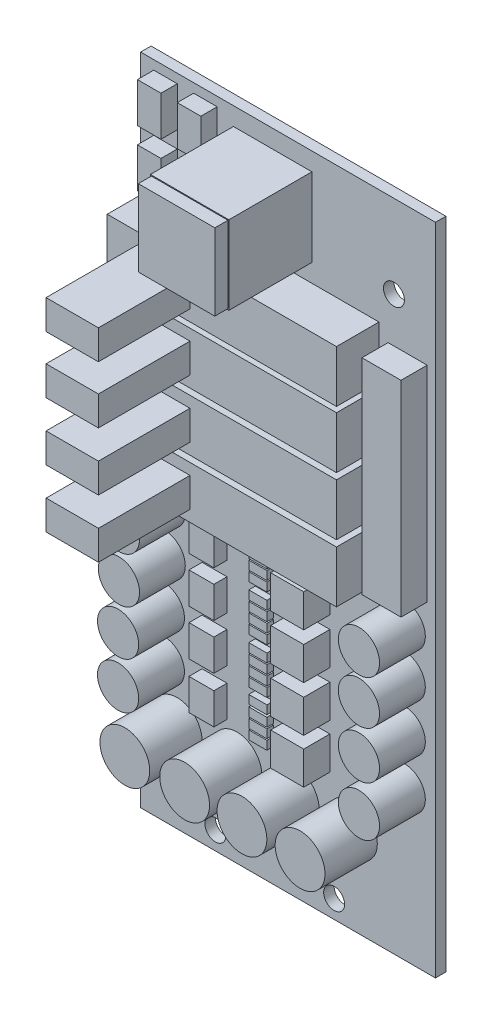
SolidWorks part; units mm, degrees
ref_plane "前视基准面" through (0, 0, 0) normal (0, 0, 1) x (1, 0, 0)
ref_plane "上视基准面" through (0, 0, 0) normal (0, 1, 0) x (1, 0, 0)
ref_plane "右视基准面" through (0, 0, 0) normal (1, 0, 0) x (0, 0, -1)
sketch "Model" plane through (0, 0, 0) normal (0, 0, 1) x (1, 0, 0)
  line L0 (45.085, 0) -> (45.085, 100)
  line L1 (0, 100.076) -> (45.085, 100.076)
  line L2 (0, 0) -> (45, 0)
  line L3 (0, 0) -> (0, 100)
  line L4 (38.354, 81.407) -> (38.354, 83.9216)
  line L5 (38.354, 83.9216) -> (43.434, 83.9216)
  line L6 (43.434, 83.9216) -> (43.434, 81.407)
  line L7 (43.434, 81.407) -> (38.354, 81.407)
  line L8 (37.846, 77.729) -> (37.846, 80.518)
  line L9 (37.846, 80.518) -> (43.815, 80.518)
  line L10 (43.815, 80.518) -> (43.815, 77.729)
  line L11 (37.846, 54.229) -> (37.846, 49.149)
  line L12 (37.846, 49.149) -> (43.815, 49.149)
  line L13 (43.815, 49.149) -> (43.815, 54.229)
  line L14 (37.846, 77.729) -> (43.846, 77.729)
  line L15 (37.846, 73.229) -> (43.846, 73.229)
  line L16 (37.846, 54.229) -> (43.846, 54.229)
  line L17 (43.846, 54.229) -> (43.846, 59.1795)
  line L18 (43.846, 59.1795) -> (43.846, 77.729)
  line L19 (37.846, 54.229) -> (37.846, 59.1795)
  line L20 (37.846, 59.1795) -> (37.846, 77.729)
  line L21 (5.715, 43.688) -> (4.699, 43.688)
  line L22 (5.207, 44.196) -> (5.207, 43.18)
  line L23 (10.421, 44.9392) -> (10.421, 45.7393)
  line L24 (11.5307, 44.6294) -> (10.7308, 44.6294)
  line L25 (11.5307, 46.049) -> (10.7308, 46.049)
  line L26 (12.1066, 44.6236) -> (12.9066, 44.6236)
  line L27 (13.2165, 44.9334) -> (13.2165, 45.7334)
  line L28 (12.1066, 46.0432) -> (12.9066, 46.0432)
  line L29 (42.418, 45.72) -> (41.402, 45.72)
  line L30 (41.91, 46.228) -> (41.91, 45.212)
  line L31 (35.6682, 45.205) -> (36.4683, 45.205)
  line L32 (35.3584, 44.0953) -> (35.3584, 44.8952)
  line L33 (36.778, 44.0953) -> (36.778, 44.8952)
  line L34 (35.3526, 43.5194) -> (35.3526, 42.7194)
  line L35 (35.6624, 42.4095) -> (36.4624, 42.4095)
  line L36 (36.7722, 43.5194) -> (36.7722, 42.7194)
  line L37 (31.757, 5.0612) -> (31.757, 5.8613)
  line L38 (32.8667, 4.7514) -> (32.0668, 4.7514)
  line L39 (32.8667, 6.171) -> (32.0668, 6.171)
  line L40 (33.4426, 4.7456) -> (34.2426, 4.7456)
  line L41 (34.5525, 5.0554) -> (34.5525, 5.8554)
  line L42 (33.4426, 6.1652) -> (34.2426, 6.1652)
  line L43 (5.715, 36.703) -> (4.699, 36.703)
  line L44 (5.207, 37.211) -> (5.207, 36.195)
  line L45 (10.548, 37.8272) -> (10.548, 38.6273)
  line L46 (11.6577, 37.5174) -> (10.8578, 37.5174)
  line L47 (11.6577, 38.937) -> (10.8578, 38.937)
  line L48 (12.2336, 37.5116) -> (13.0336, 37.5116)
  line L49 (13.3435, 37.8214) -> (13.3435, 38.6214)
  line L50 (12.2336, 38.9312) -> (13.0336, 38.9312)
  line L51 (42.418, 38.989) -> (41.402, 38.989)
  line L52 (41.91, 39.497) -> (41.91, 38.481)
  line L53 (35.6682, 39.109) -> (36.4683, 39.109)
  line L54 (35.3584, 37.9993) -> (35.3584, 38.7992)
  line L55 (36.778, 37.9993) -> (36.778, 38.7992)
  line L56 (35.3526, 37.4234) -> (35.3526, 36.6234)
  line L57 (35.6624, 36.3135) -> (36.4624, 36.3135)
  line L58 (36.7722, 37.4234) -> (36.7722, 36.6234)
  line L59 (23.248, 5.1882) -> (23.248, 5.9883)
  line L60 (24.3577, 4.8784) -> (23.5578, 4.8784)
  line L61 (24.3577, 6.298) -> (23.5578, 6.298)
  line L62 (24.9336, 4.8726) -> (25.7336, 4.8726)
  line L63 (26.0435, 5.1824) -> (26.0435, 5.9824)
  line L64 (24.9336, 6.2922) -> (25.7336, 6.2922)
  line L65 (14.231, 5.1882) -> (14.231, 5.9883)
  line L66 (15.3407, 4.8784) -> (14.5408, 4.8784)
  line L67 (15.3407, 6.298) -> (14.5408, 6.298)
  line L68 (15.9166, 4.8726) -> (16.7166, 4.8726)
  line L69 (17.0265, 5.1824) -> (17.0265, 5.9824)
  line L70 (15.9166, 6.2922) -> (16.7166, 6.2922)
  line L71 (35.7952, 32.124) -> (36.5953, 32.124)
  line L72 (35.4854, 31.0143) -> (35.4854, 31.8142)
  line L73 (36.905, 31.0143) -> (36.905, 31.8142)
  line L74 (35.4796, 30.4384) -> (35.4796, 29.6384)
  line L75 (35.7894, 29.3285) -> (36.5894, 29.3285)
  line L76 (36.8992, 30.4384) -> (36.8992, 29.6384)
  line L77 (42.418, 31.75) -> (41.402, 31.75)
  line L78 (41.91, 32.258) -> (41.91, 31.242)
  line L79 (10.548, 30.9692) -> (10.548, 31.7693)
  line L80 (11.6577, 30.6594) -> (10.8578, 30.6594)
  line L81 (11.6577, 32.079) -> (10.8578, 32.079)
  line L82 (12.2336, 30.6536) -> (13.0336, 30.6536)
  line L83 (13.3435, 30.9634) -> (13.3435, 31.7634)
  line L84 (12.2336, 32.0732) -> (13.0336, 32.0732)
  line L85 (5.588, 29.718) -> (4.572, 29.718)
  line L86 (5.08, 30.226) -> (5.08, 29.21)
  line L87 (5.588, 22.606) -> (4.572, 22.606)
  line L88 (5.08, 23.114) -> (5.08, 22.098)
  line L89 (10.421, 23.8572) -> (10.421, 24.6573)
  line L90 (11.5307, 23.5474) -> (10.7308, 23.5474)
  line L91 (11.5307, 24.967) -> (10.7308, 24.967)
  line L92 (12.1066, 23.5416) -> (12.9066, 23.5416)
  line L93 (13.2165, 23.8514) -> (13.2165, 24.6514)
  line L94 (12.1066, 24.9612) -> (12.9066, 24.9612)
  line L95 (42.418, 24.13) -> (41.402, 24.13)
  line L96 (41.91, 24.638) -> (41.91, 23.622)
  line L97 (35.6682, 24.758) -> (36.4683, 24.758)
  line L98 (35.3584, 23.6483) -> (35.3584, 24.4482)
  line L99 (36.778, 23.6483) -> (36.778, 24.4482)
  line L100 (35.3526, 23.0724) -> (35.3526, 22.2724)
  line L101 (35.6624, 21.9625) -> (36.4624, 21.9625)
  line L102 (36.7722, 23.0724) -> (36.7722, 22.2724)
  line L103 (5.087, 5.1882) -> (5.087, 5.9883)
  line L104 (6.1967, 4.8784) -> (5.3968, 4.8784)
  line L105 (6.1967, 6.298) -> (5.3968, 6.298)
  line L106 (6.7726, 4.8726) -> (7.5726, 4.8726)
  line L107 (7.8825, 5.1824) -> (7.8825, 5.9824)
  line L108 (6.7726, 6.2922) -> (7.5726, 6.2922)
  line L109 (31.9707, 46.6432) -> (31.9707, 41.2408)
  line L110 (29.2433, 46.6432) -> (29.2433, 41.2408)
  line L111 (31.9707, 45.281) -> (29.2433, 45.281)
  line L112 (31.9707, 41.2408) -> (31.6202, 41.2408)
  line L113 (29.2433, 41.2408) -> (29.5938, 41.2408)
  line L114 (34.4128, 42.0492) -> (37.2152, 42.0492)
  line L115 (37.2152, 42.0492) -> (37.2152, 41.7712)
  line L116 (34.4128, 40.2468) -> (37.2152, 40.2468)
  line L117 (37.2152, 40.2468) -> (37.2152, 40.5248)
  line L118 (34.8422, 42.0492) -> (34.8422, 40.2468)
  line L119 (31.9707, 39.2772) -> (31.9707, 33.8748)
  line L120 (29.2433, 39.2772) -> (29.2433, 33.8748)
  line L121 (31.9707, 37.915) -> (29.2433, 37.915)
  line L122 (31.9707, 33.8748) -> (31.6202, 33.8748)
  line L123 (29.2433, 33.8748) -> (29.5938, 33.8748)
  line L124 (34.4128, 35.8262) -> (37.2152, 35.8262)
  line L125 (37.2152, 35.8262) -> (37.2152, 35.5482)
  line L126 (34.4128, 34.0238) -> (37.2152, 34.0238)
  line L127 (37.2152, 34.0238) -> (37.2152, 34.3018)
  line L128 (34.8422, 35.8262) -> (34.8422, 34.0238)
  line L129 (34.4128, 28.2062) -> (37.2152, 28.2062)
  line L130 (37.2152, 28.2062) -> (37.2152, 27.9282)
  line L131 (34.4128, 26.4038) -> (37.2152, 26.4038)
  line L132 (37.2152, 26.4038) -> (37.2152, 26.6818)
  line L133 (34.8422, 28.2062) -> (34.8422, 26.4038)
  line L134 (31.9707, 31.7842) -> (31.9707, 26.3818)
  line L135 (29.2433, 31.7842) -> (29.2433, 26.3818)
  line L136 (31.9707, 30.422) -> (29.2433, 30.422)
  line L137 (31.9707, 26.3818) -> (31.6202, 26.3818)
  line L138 (29.2433, 26.3818) -> (29.5938, 26.3818)
  line L139 (31.9707, 24.2912) -> (31.9707, 18.8888)
  line L140 (29.2433, 24.2912) -> (29.2433, 18.8888)
  line L141 (31.9707, 22.929) -> (29.2433, 22.929)
  line L142 (31.9707, 18.8888) -> (31.6202, 18.8888)
  line L143 (29.2433, 18.8888) -> (29.5938, 18.8888)
  line L144 (34.5398, 20.7132) -> (37.3422, 20.7132)
  line L145 (37.3422, 20.7132) -> (37.3422, 20.4352)
  line L146 (34.5398, 18.9108) -> (37.3422, 18.9108)
  line L147 (37.3422, 18.9108) -> (37.3422, 19.1888)
  line L148 (34.9692, 20.7132) -> (34.9692, 18.9108)
  line L149 (44.3189, 4.445) -> (44.3189, 5.695)
  line L150 (44.3189, 5.695) -> (42.3189, 5.695)
  line L151 (44.4459, -0.432) -> (35.3779, -0.432)
  line L152 (35.3787, 4.3548) -> (35.3787, 5.6045)
  line L153 (35.3787, 5.6045) -> (37.3777, 5.6045)
  line L154 (44.4459, 1.524) -> (44.4459, -0.4379)
  line L155 (35.3779, -0.382) -> (35.3779, 1.605)
  line L156 (34.925, 9.144) -> (34.925, 6.6294)
  line L157 (34.925, 6.6294) -> (29.845, 6.6294)
  line L158 (29.845, 6.6294) -> (29.845, 9.144)
  line L159 (29.845, 9.144) -> (34.925, 9.144)
  line L160 (26.035, 9.144) -> (26.035, 6.6294)
  line L161 (26.035, 6.6294) -> (20.955, 6.6294)
  line L162 (20.955, 6.6294) -> (20.955, 9.144)
  line L163 (20.955, 9.144) -> (26.035, 9.144)
  line L164 (17.018, 9.144) -> (17.018, 6.6294)
  line L165 (17.018, 6.6294) -> (11.938, 6.6294)
  line L166 (11.938, 6.6294) -> (11.938, 9.144)
  line L167 (11.938, 9.144) -> (17.018, 9.144)
  line L168 (7.874, 9.144) -> (7.874, 6.6294)
  line L169 (7.874, 6.6294) -> (2.794, 6.6294)
  line L170 (2.794, 6.6294) -> (2.794, 9.144)
  line L171 (2.794, 9.144) -> (7.874, 9.144)
  line L172 (33.909, 96.266) -> (33.909, 98.806)
  line L173 (33.909, 98.806) -> (44.069, 98.806)
  line L174 (44.069, 98.806) -> (44.069, 96.266)
  line L175 (44.069, 96.266) -> (42.164, 96.266)
  line L176 (33.909, 96.266) -> (42.164, 96.266)
  line L177 (33.909, 93.726) -> (33.909, 96.266)
  line L178 (33.909, 96.266) -> (44.069, 96.266)
  line L179 (44.069, 96.266) -> (44.069, 93.726)
  line L180 (44.069, 93.726) -> (42.164, 93.726)
  line L181 (33.909, 93.726) -> (42.164, 93.726)
  line L182 (6.731, 0.889) -> (8.636, 0.889)
  line L183 (8.636, 0.889) -> (8.636, 3.429)
  line L184 (8.636, 3.429) -> (1.016, 3.429)
  line L185 (1.016, 3.429) -> (1.016, 0.889)
  line L186 (1.016, 0.889) -> (6.731, 0.889)
  line L187 (24.1536, 40.0188) -> (23.8898, 40.0188)
  line L188 (23.8898, 40.0188) -> (23.8898, 45.0712)
  line L189 (23.8898, 45.0712) -> (24.1536, 45.0712)
  line L190 (28.6784, 40.0188) -> (28.9422, 40.0188)
  line L191 (28.9422, 40.0188) -> (28.9422, 45.0712)
  line L192 (28.9422, 45.0712) -> (28.6784, 45.0712)
  line L193 (24.1536, 33.0338) -> (23.8898, 33.0338)
  line L194 (23.8898, 33.0338) -> (23.8898, 38.0862)
  line L195 (23.8898, 38.0862) -> (24.1536, 38.0862)
  line L196 (28.6784, 33.0338) -> (28.9422, 33.0338)
  line L197 (28.9422, 33.0338) -> (28.9422, 38.0862)
  line L198 (28.9422, 38.0862) -> (28.6784, 38.0862)
  line L199 (24.1536, 26.0488) -> (23.8898, 26.0488)
  line L200 (23.8898, 26.0488) -> (23.8898, 31.1012)
  line L201 (23.8898, 31.1012) -> (24.1536, 31.1012)
  line L202 (28.6784, 26.0488) -> (28.9422, 26.0488)
  line L203 (28.9422, 26.0488) -> (28.9422, 31.1012)
  line L204 (28.9422, 31.1012) -> (28.6784, 31.1012)
  line L205 (24.1536, 19.1908) -> (23.8898, 19.1908)
  line L206 (23.8898, 19.1908) -> (23.8898, 24.2432)
  line L207 (23.8898, 24.2432) -> (24.1536, 24.2432)
  line L208 (28.6784, 19.1908) -> (28.9422, 19.1908)
  line L209 (28.9422, 19.1908) -> (28.9422, 24.2432)
  line L210 (28.9422, 24.2432) -> (28.6784, 24.2432)
  line L211 (23.6242, 40.0408) -> (23.6242, 41.4932)
  line L212 (23.6242, 41.4932) -> (22.5926, 41.4932)
  line L213 (20.5718, 40.0408) -> (20.5718, 41.4932)
  line L214 (20.5718, 41.4932) -> (21.6034, 41.4932)
  line L215 (22.5534, 40.0408) -> (21.6426, 40.0408)
  line L216 (23.6242, 43.5968) -> (23.6242, 45.0492)
  line L217 (23.6242, 45.0492) -> (22.5926, 45.0492)
  line L218 (20.5718, 43.5968) -> (20.5718, 45.0492)
  line L219 (20.5718, 45.0492) -> (21.6034, 45.0492)
  line L220 (22.5534, 43.5968) -> (21.6426, 43.5968)
  line L221 (23.6242, 33.0558) -> (23.6242, 34.5082)
  line L222 (23.6242, 34.5082) -> (22.5926, 34.5082)
  line L223 (20.5718, 33.0558) -> (20.5718, 34.5082)
  line L224 (20.5718, 34.5082) -> (21.6034, 34.5082)
  line L225 (22.5534, 33.0558) -> (21.6426, 33.0558)
  line L226 (23.6242, 36.6118) -> (23.6242, 38.0642)
  line L227 (23.6242, 38.0642) -> (22.5926, 38.0642)
  line L228 (20.5718, 36.6118) -> (20.5718, 38.0642)
  line L229 (20.5718, 38.0642) -> (21.6034, 38.0642)
  line L230 (22.5534, 36.6118) -> (21.6426, 36.6118)
  line L231 (23.6242, 29.6268) -> (23.6242, 31.0792)
  line L232 (23.6242, 31.0792) -> (22.5926, 31.0792)
  line L233 (20.5718, 29.6268) -> (20.5718, 31.0792)
  line L234 (20.5718, 31.0792) -> (21.6034, 31.0792)
  line L235 (22.5534, 29.6268) -> (21.6426, 29.6268)
  line L236 (23.6242, 26.3248) -> (23.6242, 27.7772)
  line L237 (23.6242, 27.7772) -> (22.5926, 27.7772)
  line L238 (20.5718, 26.3248) -> (20.5718, 27.7772)
  line L239 (20.5718, 27.7772) -> (21.6034, 27.7772)
  line L240 (22.5534, 26.3248) -> (21.6426, 26.3248)
  line L241 (23.6242, 19.5938) -> (23.6242, 21.0462)
  line L242 (23.6242, 21.0462) -> (22.5926, 21.0462)
  line L243 (20.5718, 19.5938) -> (20.5718, 21.0462)
  line L244 (20.5718, 21.0462) -> (21.6034, 21.0462)
  line L245 (22.5534, 19.5938) -> (21.6426, 19.5938)
  line L246 (23.6242, 22.8958) -> (23.6242, 24.3482)
  line L247 (23.6242, 24.3482) -> (22.5926, 24.3482)
  line L248 (20.5718, 22.8958) -> (20.5718, 24.3482)
  line L249 (20.5718, 24.3482) -> (21.6034, 24.3482)
  line L250 (22.5534, 22.8958) -> (21.6426, 22.8958)
  line L251 (13.8686, 85.3892) -> (13.8686, 86.3481)
  line L252 (13.8686, 86.3481) -> (12.5474, 86.3481)
  line L253 (12.5474, 86.3481) -> (12.5474, 85.3892)
  line L254 (13.8686, 84.5368) -> (13.8686, 83.5779)
  line L255 (13.8686, 83.5779) -> (12.5474, 83.5779)
  line L256 (12.5474, 83.5779) -> (12.5474, 84.5368)
  line L257 (16.1742, 83.5404) -> (17.1331, 83.5404)
  line L258 (17.1331, 83.5404) -> (17.1331, 84.8616)
  line L259 (17.1331, 84.8616) -> (16.1742, 84.8616)
  line L260 (15.3218, 83.5404) -> (14.3629, 83.5404)
  line L261 (14.3629, 83.5404) -> (14.3629, 84.8616)
  line L262 (14.3629, 84.8616) -> (15.3218, 84.8616)
  line L263 (19.3492, 43.7894) -> (20.3081, 43.7894)
  line L264 (20.3081, 43.7894) -> (20.3081, 45.1106)
  line L265 (20.3081, 45.1106) -> (19.3492, 45.1106)
  line L266 (18.4968, 43.7894) -> (17.5379, 43.7894)
  line L267 (17.5379, 43.7894) -> (17.5379, 45.1106)
  line L268 (17.5379, 45.1106) -> (18.4968, 45.1106)
  line L269 (18.4968, 43.5866) -> (17.5379, 43.5866)
  line L270 (17.5379, 43.5866) -> (17.5379, 42.2654)
  line L271 (17.5379, 42.2654) -> (18.4968, 42.2654)
  line L272 (19.3492, 43.5866) -> (20.3081, 43.5866)
  line L273 (20.3081, 43.5866) -> (20.3081, 42.2654)
  line L274 (20.3081, 42.2654) -> (19.3492, 42.2654)
  line L275 (35.0776, 44.2412) -> (35.0776, 45.2001)
  line L276 (35.0776, 45.2001) -> (33.7564, 45.2001)
  line L277 (33.7564, 45.2001) -> (33.7564, 44.2412)
  line L278 (35.0776, 43.3888) -> (35.0776, 42.4299)
  line L279 (35.0776, 42.4299) -> (33.7564, 42.4299)
  line L280 (33.7564, 42.4299) -> (33.7564, 43.3888)
  line L281 (33.5536, 44.2412) -> (33.5536, 45.2001)
  line L282 (33.5536, 45.2001) -> (32.2324, 45.2001)
  line L283 (32.2324, 45.2001) -> (32.2324, 44.2412)
  line L284 (33.5536, 43.3888) -> (33.5536, 42.4299)
  line L285 (33.5536, 42.4299) -> (32.2324, 42.4299)
  line L286 (32.2324, 42.4299) -> (32.2324, 43.3888)
  line L287 (33.5536, 41.1932) -> (33.5536, 42.1521)
  line L288 (33.5536, 42.1521) -> (32.2324, 42.1521)
  line L289 (32.2324, 42.1521) -> (32.2324, 41.1932)
  line L290 (33.5536, 40.3408) -> (33.5536, 39.3819)
  line L291 (33.5536, 39.3819) -> (32.2324, 39.3819)
  line L292 (32.2324, 39.3819) -> (32.2324, 40.3408)
  line L293 (19.3492, 40.7414) -> (20.3081, 40.7414)
  line L294 (20.3081, 40.7414) -> (20.3081, 42.0626)
  line L295 (20.3081, 42.0626) -> (19.3492, 42.0626)
  line L296 (18.4968, 40.7414) -> (17.5379, 40.7414)
  line L297 (17.5379, 40.7414) -> (17.5379, 42.0626)
  line L298 (17.5379, 42.0626) -> (18.4968, 42.0626)
  line L299 (18.4968, 40.5386) -> (17.5379, 40.5386)
  line L300 (17.5379, 40.5386) -> (17.5379, 39.2174)
  line L301 (17.5379, 39.2174) -> (18.4968, 39.2174)
  line L302 (19.3492, 40.5386) -> (20.3081, 40.5386)
  line L303 (20.3081, 40.5386) -> (20.3081, 39.2174)
  line L304 (20.3081, 39.2174) -> (19.3492, 39.2174)
  line L305 (19.3492, 36.8044) -> (20.3081, 36.8044)
  line L306 (20.3081, 36.8044) -> (20.3081, 38.1256)
  line L307 (20.3081, 38.1256) -> (19.3492, 38.1256)
  line L308 (18.4968, 36.8044) -> (17.5379, 36.8044)
  line L309 (17.5379, 36.8044) -> (17.5379, 38.1256)
  line L310 (17.5379, 38.1256) -> (18.4968, 38.1256)
  line L311 (18.4968, 36.6016) -> (17.5379, 36.6016)
  line L312 (17.5379, 36.6016) -> (17.5379, 35.2804)
  line L313 (17.5379, 35.2804) -> (18.4968, 35.2804)
  line L314 (19.3492, 36.6016) -> (20.3081, 36.6016)
  line L315 (20.3081, 36.6016) -> (20.3081, 35.2804)
  line L316 (20.3081, 35.2804) -> (19.3492, 35.2804)
  line L317 (35.0776, 38.1452) -> (35.0776, 39.1041)
  line L318 (35.0776, 39.1041) -> (33.7564, 39.1041)
  line L319 (33.7564, 39.1041) -> (33.7564, 38.1452)
  line L320 (35.0776, 37.2928) -> (35.0776, 36.3339)
  line L321 (35.0776, 36.3339) -> (33.7564, 36.3339)
  line L322 (33.7564, 36.3339) -> (33.7564, 37.2928)
  line L323 (33.5536, 38.1452) -> (33.5536, 39.1041)
  line L324 (33.5536, 39.1041) -> (32.2324, 39.1041)
  line L325 (32.2324, 39.1041) -> (32.2324, 38.1452)
  line L326 (33.5536, 37.2928) -> (33.5536, 36.3339)
  line L327 (33.5536, 36.3339) -> (32.2324, 36.3339)
  line L328 (32.2324, 36.3339) -> (32.2324, 37.2928)
  line L329 (33.5536, 35.0972) -> (33.5536, 36.0561)
  line L330 (33.5536, 36.0561) -> (32.2324, 36.0561)
  line L331 (32.2324, 36.0561) -> (32.2324, 35.0972)
  line L332 (33.5536, 34.2448) -> (33.5536, 33.2859)
  line L333 (33.5536, 33.2859) -> (32.2324, 33.2859)
  line L334 (32.2324, 33.2859) -> (32.2324, 34.2448)
  line L335 (19.3492, 33.7564) -> (20.3081, 33.7564)
  line L336 (20.3081, 33.7564) -> (20.3081, 35.0776)
  line L337 (20.3081, 35.0776) -> (19.3492, 35.0776)
  line L338 (18.4968, 33.7564) -> (17.5379, 33.7564)
  line L339 (17.5379, 33.7564) -> (17.5379, 35.0776)
  line L340 (17.5379, 35.0776) -> (18.4968, 35.0776)
  line L341 (18.4968, 33.5536) -> (17.5379, 33.5536)
  line L342 (17.5379, 33.5536) -> (17.5379, 32.2324)
  line L343 (17.5379, 32.2324) -> (18.4968, 32.2324)
  line L344 (19.3492, 33.5536) -> (20.3081, 33.5536)
  line L345 (20.3081, 33.5536) -> (20.3081, 32.2324)
  line L346 (20.3081, 32.2324) -> (19.3492, 32.2324)
  line L347 (18.4968, 26.5686) -> (17.5379, 26.5686)
  line L348 (17.5379, 26.5686) -> (17.5379, 25.2474)
  line L349 (17.5379, 25.2474) -> (18.4968, 25.2474)
  line L350 (19.3492, 26.5686) -> (20.3081, 26.5686)
  line L351 (20.3081, 26.5686) -> (20.3081, 25.2474)
  line L352 (20.3081, 25.2474) -> (19.3492, 25.2474)
  line L353 (19.3492, 26.7714) -> (20.3081, 26.7714)
  line L354 (20.3081, 26.7714) -> (20.3081, 28.0926)
  line L355 (20.3081, 28.0926) -> (19.3492, 28.0926)
  line L356 (18.4968, 26.7714) -> (17.5379, 26.7714)
  line L357 (17.5379, 26.7714) -> (17.5379, 28.0926)
  line L358 (17.5379, 28.0926) -> (18.4968, 28.0926)
  line L359 (33.5536, 28.1122) -> (33.5536, 29.0711)
  line L360 (33.5536, 29.0711) -> (32.2324, 29.0711)
  line L361 (32.2324, 29.0711) -> (32.2324, 28.1122)
  line L362 (33.5536, 27.2598) -> (33.5536, 26.3009)
  line L363 (33.5536, 26.3009) -> (32.2324, 26.3009)
  line L364 (32.2324, 26.3009) -> (32.2324, 27.2598)
  line L365 (33.5536, 31.1602) -> (33.5536, 32.1191)
  line L366 (33.5536, 32.1191) -> (32.2324, 32.1191)
  line L367 (32.2324, 32.1191) -> (32.2324, 31.1602)
  line L368 (33.5536, 30.3078) -> (33.5536, 29.3489)
  line L369 (33.5536, 29.3489) -> (32.2324, 29.3489)
  line L370 (32.2324, 29.3489) -> (32.2324, 30.3078)
  line L371 (35.2046, 31.1602) -> (35.2046, 32.1191)
  line L372 (35.2046, 32.1191) -> (33.8834, 32.1191)
  line L373 (33.8834, 32.1191) -> (33.8834, 31.1602)
  line L374 (35.2046, 30.3078) -> (35.2046, 29.3489)
  line L375 (35.2046, 29.3489) -> (33.8834, 29.3489)
  line L376 (33.8834, 29.3489) -> (33.8834, 30.3078)
  line L377 (18.4968, 29.6166) -> (17.5379, 29.6166)
  line L378 (17.5379, 29.6166) -> (17.5379, 28.2954)
  line L379 (17.5379, 28.2954) -> (18.4968, 28.2954)
  line L380 (19.3492, 29.6166) -> (20.3081, 29.6166)
  line L381 (20.3081, 29.6166) -> (20.3081, 28.2954)
  line L382 (20.3081, 28.2954) -> (19.3492, 28.2954)
  line L383 (19.3492, 29.8194) -> (20.3081, 29.8194)
  line L384 (20.3081, 29.8194) -> (20.3081, 31.1406)
  line L385 (20.3081, 31.1406) -> (19.3492, 31.1406)
  line L386 (18.4968, 29.8194) -> (17.5379, 29.8194)
  line L387 (17.5379, 29.8194) -> (17.5379, 31.1406)
  line L388 (17.5379, 31.1406) -> (18.4968, 31.1406)
  line L389 (19.3492, 22.9614) -> (20.3081, 22.9614)
  line L390 (20.3081, 22.9614) -> (20.3081, 24.2826)
  line L391 (20.3081, 24.2826) -> (19.3492, 24.2826)
  line L392 (18.4968, 22.9614) -> (17.5379, 22.9614)
  line L393 (17.5379, 22.9614) -> (17.5379, 24.2826)
  line L394 (17.5379, 24.2826) -> (18.4968, 24.2826)
  line L395 (18.4968, 22.6316) -> (17.5379, 22.6316)
  line L396 (17.5379, 22.6316) -> (17.5379, 21.3104)
  line L397 (17.5379, 21.3104) -> (18.4968, 21.3104)
  line L398 (19.3492, 22.6316) -> (20.3081, 22.6316)
  line L399 (20.3081, 22.6316) -> (20.3081, 21.3104)
  line L400 (20.3081, 21.3104) -> (19.3492, 21.3104)
  line L401 (35.0776, 23.7942) -> (35.0776, 24.7531)
  line L402 (35.0776, 24.7531) -> (33.7564, 24.7531)
  line L403 (33.7564, 24.7531) -> (33.7564, 23.7942)
  line L404 (35.0776, 22.9418) -> (35.0776, 21.9829)
  line L405 (35.0776, 21.9829) -> (33.7564, 21.9829)
  line L406 (33.7564, 21.9829) -> (33.7564, 22.9418)
  line L407 (33.5536, 23.7942) -> (33.5536, 24.7531)
  line L408 (33.5536, 24.7531) -> (32.2324, 24.7531)
  line L409 (32.2324, 24.7531) -> (32.2324, 23.7942)
  line L410 (33.5536, 22.9418) -> (33.5536, 21.9829)
  line L411 (33.5536, 21.9829) -> (32.2324, 21.9829)
  line L412 (32.2324, 21.9829) -> (32.2324, 22.9418)
  line L413 (33.5536, 20.7462) -> (33.5536, 21.7051)
  line L414 (33.5536, 21.7051) -> (32.2324, 21.7051)
  line L415 (32.2324, 21.7051) -> (32.2324, 20.7462)
  line L416 (33.5536, 19.8938) -> (33.5536, 18.9349)
  line L417 (33.5536, 18.9349) -> (32.2324, 18.9349)
  line L418 (32.2324, 18.9349) -> (32.2324, 19.8938)
  line L419 (19.3492, 19.7864) -> (20.3081, 19.7864)
  line L420 (20.3081, 19.7864) -> (20.3081, 21.1076)
  line L421 (20.3081, 21.1076) -> (19.3492, 21.1076)
  line L422 (18.4968, 19.7864) -> (17.5379, 19.7864)
  line L423 (17.5379, 19.7864) -> (17.5379, 21.1076)
  line L424 (17.5379, 21.1076) -> (18.4968, 21.1076)
  line L425 (18.4968, 19.5836) -> (17.5379, 19.5836)
  line L426 (17.5379, 19.5836) -> (17.5379, 18.2624)
  line L427 (17.5379, 18.2624) -> (18.4968, 18.2624)
  line L428 (19.3492, 19.5836) -> (20.3081, 19.5836)
  line L429 (20.3081, 19.5836) -> (20.3081, 18.2624)
  line L430 (20.3081, 18.2624) -> (19.3492, 18.2624)
  line L431 (23.3438, 97.313) -> (14.193, 97.313)
  line L432 (26.193, 95.2728) -> (26.193, 97.313)
  line L433 (26.193, 97.313) -> (24.6422, 97.313)
  line L434 (26.193, 90.2728) -> (26.193, 92.3532)
  line L435 (17.0422, 85.313) -> (26.193, 85.313)
  line L436 (26.193, 85.313) -> (26.193, 87.3532)
  line L437 (14.193, 87.3532) -> (14.193, 85.313)
  line L438 (14.193, 85.313) -> (15.7438, 85.313)
  line L439 (14.193, 92.3532) -> (14.193, 90.2728)
  line L440 (14.193, 97.313) -> (14.193, 95.2728)
  line L441 (8.106, 83.945) -> (8.106, 90.045)
  line L442 (11.706, 83.945) -> (11.706, 90.045)
  line L443 (8.636, 84.455) -> (8.636, 89.535)
  line L444 (8.636, 89.535) -> (9.1749, 89.535)
  line L445 (8.106, 83.945) -> (9.1749, 83.945)
  line L446 (10.6371, 83.945) -> (11.706, 83.945)
  line L447 (8.106, 90.045) -> (9.1749, 90.045)
  line L448 (10.6371, 90.045) -> (11.706, 90.045)
  line L449 (10.6371, 89.535) -> (11.176, 89.535)
  line L450 (11.176, 89.535) -> (11.176, 84.455)
  line L451 (11.176, 84.455) -> (10.6371, 84.455)
  line L452 (9.1749, 84.455) -> (8.636, 84.455)
  line L453 (9.271, 85.725) -> (9.271, 88.392)
  line L454 (9.271, 88.392) -> (10.541, 88.392)
  line L455 (10.541, 88.392) -> (10.541, 85.725)
  line L456 (10.541, 85.725) -> (9.271, 85.725)
  line L457 (8.106, 92.581) -> (8.106, 98.681)
  line L458 (11.706, 92.581) -> (11.706, 98.681)
  line L459 (8.636, 93.091) -> (8.636, 98.171)
  line L460 (8.636, 98.171) -> (9.1749, 98.171)
  line L461 (8.106, 92.581) -> (9.1749, 92.581)
  line L462 (10.6371, 92.581) -> (11.706, 92.581)
  line L463 (8.106, 98.681) -> (9.1749, 98.681)
  line L464 (10.6371, 98.681) -> (11.706, 98.681)
  line L465 (10.6371, 98.171) -> (11.176, 98.171)
  line L466 (11.176, 98.171) -> (11.176, 93.091)
  line L467 (11.176, 93.091) -> (10.6371, 93.091)
  line L468 (9.1749, 93.091) -> (8.636, 93.091)
  line L469 (9.271, 94.361) -> (9.271, 97.028)
  line L470 (9.271, 97.028) -> (10.541, 97.028)
  line L471 (10.541, 97.028) -> (10.541, 94.361)
  line L472 (10.541, 94.361) -> (9.271, 94.361)
  line L473 (2.01, 92.581) -> (2.01, 98.681)
  line L474 (5.61, 92.581) -> (5.61, 98.681)
  line L475 (2.54, 93.091) -> (2.54, 98.171)
  line L476 (2.54, 98.171) -> (3.0789, 98.171)
  line L477 (2.01, 92.581) -> (3.0789, 92.581)
  line L478 (4.5411, 92.581) -> (5.61, 92.581)
  line L479 (2.01, 98.681) -> (3.0789, 98.681)
  line L480 (4.5411, 98.681) -> (5.61, 98.681)
  line L481 (4.5411, 98.171) -> (5.08, 98.171)
  line L482 (5.08, 98.171) -> (5.08, 93.091)
  line L483 (5.08, 93.091) -> (4.5411, 93.091)
  line L484 (3.0789, 93.091) -> (2.54, 93.091)
  line L485 (3.175, 94.361) -> (3.175, 97.028)
  line L486 (3.175, 97.028) -> (4.445, 97.028)
  line L487 (4.445, 97.028) -> (4.445, 94.361)
  line L488 (4.445, 94.361) -> (3.175, 94.361)
  line L489 (2.01, 83.945) -> (2.01, 90.045)
  line L490 (5.61, 83.945) -> (5.61, 90.045)
  line L491 (2.54, 84.455) -> (2.54, 89.535)
  line L492 (2.54, 89.535) -> (3.0789, 89.535)
  line L493 (2.01, 83.945) -> (3.0789, 83.945)
  line L494 (4.5411, 83.945) -> (5.61, 83.945)
  line L495 (2.01, 90.045) -> (3.0789, 90.045)
  line L496 (4.5411, 90.045) -> (5.61, 90.045)
  line L497 (4.5411, 89.535) -> (5.08, 89.535)
  line L498 (5.08, 89.535) -> (5.08, 84.455)
  line L499 (5.08, 84.455) -> (4.5411, 84.455)
  line L500 (3.0789, 84.455) -> (2.54, 84.455)
  line L501 (3.175, 85.725) -> (3.175, 88.392)
  line L502 (3.175, 88.392) -> (4.445, 88.392)
  line L503 (4.445, 88.392) -> (4.445, 85.725)
  line L504 (4.445, 85.725) -> (3.175, 85.725)
  line L505 (12.703, 44.183) -> (9.398, 44.183)
  line L506 (9.398, 44.183) -> (9.398, 39.383)
  line L507 (9.398, 39.383) -> (13.208, 39.383)
  line L508 (13.208, 39.383) -> (13.208, 44.183)
  line L509 (13.208, 44.183) -> (12.703, 44.183)
  line L510 (12.703, 37.198) -> (9.398, 37.198)
  line L511 (9.398, 37.198) -> (9.398, 32.398)
  line L512 (9.398, 32.398) -> (13.208, 32.398)
  line L513 (13.208, 32.398) -> (13.208, 37.198)
  line L514 (13.208, 37.198) -> (12.703, 37.198)
  line L515 (12.703, 30.213) -> (9.398, 30.213)
  line L516 (9.398, 30.213) -> (9.398, 25.413)
  line L517 (9.398, 25.413) -> (13.208, 25.413)
  line L518 (13.208, 25.413) -> (13.208, 30.213)
  line L519 (13.208, 30.213) -> (12.703, 30.213)
  line L520 (12.703, 23.101) -> (9.398, 23.101)
  line L521 (9.398, 23.101) -> (9.398, 18.301)
  line L522 (9.398, 18.301) -> (13.208, 18.301)
  line L523 (13.208, 18.301) -> (13.208, 23.101)
  line L524 (13.208, 23.101) -> (12.703, 23.101)
  line L525 (11.303, 76.2001) -> (11.303, 81.0261)
  line L526 (11.303, 81.0261) -> (11.176, 81.1531)
  line L527 (13.843, 81.0261) -> (13.843, 76.2001)
  line L528 (1.397, 74.613) -> (36.449, 74.613)
  line L529 (36.449, 74.613) -> (36.449, 82.5501)
  line L530 (36.449, 82.5501) -> (1.397, 82.5501)
  line L531 (1.397, 74.613) -> (1.397, 82.613)
  line L532 (29.0829, 76.073) -> (8.6359, 76.073)
  line L533 (8.6359, 76.073) -> (8.6359, 81.153)
  line L534 (8.6359, 81.153) -> (29.0829, 81.153)
  line L535 (29.0829, 81.153) -> (29.0829, 76.073)
  line L536 (11.303, 67.4371) -> (11.303, 72.2631)
  line L537 (11.303, 72.2631) -> (11.176, 72.3901)
  line L538 (13.843, 72.2631) -> (13.843, 67.4371)
  line L539 (1.397, 65.85) -> (36.449, 65.85)
  line L540 (36.449, 65.85) -> (36.449, 73.7871)
  line L541 (36.449, 73.7871) -> (1.397, 73.7871)
  line L542 (1.397, 65.85) -> (1.397, 73.85)
  line L543 (29.0829, 67.31) -> (8.6359, 67.31)
  line L544 (8.6359, 67.31) -> (8.6359, 72.39)
  line L545 (8.6359, 72.39) -> (29.0829, 72.39)
  line L546 (29.0829, 72.39) -> (29.0829, 67.31)
  line L547 (11.303, 58.5471) -> (11.303, 63.3731)
  line L548 (11.303, 63.3731) -> (11.176, 63.5001)
  line L549 (13.843, 63.3731) -> (13.843, 58.5471)
  line L550 (1.397, 56.96) -> (36.449, 56.96)
  line L551 (36.449, 56.96) -> (36.449, 64.8971)
  line L552 (36.449, 64.8971) -> (1.397, 64.8971)
  line L553 (1.397, 56.96) -> (1.397, 64.96)
  line L554 (29.0829, 58.42) -> (8.6359, 58.42)
  line L555 (8.6359, 58.42) -> (8.6359, 63.5)
  line L556 (8.6359, 63.5) -> (29.0829, 63.5)
  line L557 (29.0829, 63.5) -> (29.0829, 58.42)
  line L558 (11.303, 49.6571) -> (11.303, 54.4831)
  line L559 (11.303, 54.4831) -> (11.176, 54.6101)
  line L560 (13.843, 54.4831) -> (13.843, 49.6571)
  line L561 (1.397, 48.07) -> (36.449, 48.07)
  line L562 (36.449, 48.07) -> (36.449, 56.0071)
  line L563 (36.449, 56.0071) -> (1.397, 56.0071)
  line L564 (1.397, 48.07) -> (1.397, 56.07)
  line L565 (29.0829, 49.53) -> (8.6359, 49.53)
  line L566 (8.6359, 49.53) -> (8.6359, 54.61)
  line L567 (8.6359, 54.61) -> (29.0829, 54.61)
  line L568 (29.0829, 54.61) -> (29.0829, 49.53)
  line L569 (45.085, 0) -> (45.085, 100)
  arc A0 (12.9067, 44.6236) -> (13.2165, 44.9334) centre (12.9067, 44.9334) ccw
  arc A1 (13.2165, 45.7334) -> (12.9067, 46.0432) centre (12.9067, 45.7334) ccw
  arc A2 (10.421, 44.9392) -> (10.7308, 44.6294) centre (10.7308, 44.9392) ccw
  arc A3 (10.7308, 46.049) -> (10.421, 45.7392) centre (10.7308, 45.7392) ccw
  arc A4 (35.3526, 42.7193) -> (35.6624, 42.4095) centre (35.6624, 42.7193) ccw
  arc A5 (36.4624, 42.4095) -> (36.7722, 42.7193) centre (36.4624, 42.7193) ccw
  arc A6 (35.6682, 45.205) -> (35.3584, 44.8952) centre (35.6682, 44.8952) ccw
  arc A7 (36.778, 44.8952) -> (36.4682, 45.205) centre (36.4682, 44.8952) ccw
  arc A8 (34.2427, 4.7456) -> (34.5525, 5.0554) centre (34.2427, 5.0554) ccw
  arc A9 (34.5525, 5.8554) -> (34.2427, 6.1652) centre (34.2427, 5.8554) ccw
  arc A10 (31.757, 5.0612) -> (32.0668, 4.7514) centre (32.0668, 5.0612) ccw
  arc A11 (32.0668, 6.171) -> (31.757, 5.8612) centre (32.0668, 5.8612) ccw
  arc A12 (13.0337, 37.5116) -> (13.3435, 37.8214) centre (13.0337, 37.8214) ccw
  arc A13 (13.3435, 38.6214) -> (13.0337, 38.9312) centre (13.0337, 38.6214) ccw
  arc A14 (10.548, 37.8272) -> (10.8578, 37.5174) centre (10.8578, 37.8272) ccw
  arc A15 (10.8578, 38.937) -> (10.548, 38.6272) centre (10.8578, 38.6272) ccw
  arc A16 (35.3526, 36.6233) -> (35.6624, 36.3135) centre (35.6624, 36.6233) ccw
  arc A17 (36.4624, 36.3135) -> (36.7722, 36.6233) centre (36.4624, 36.6233) ccw
  arc A18 (35.6682, 39.109) -> (35.3584, 38.7992) centre (35.6682, 38.7992) ccw
  arc A19 (36.778, 38.7992) -> (36.4682, 39.109) centre (36.4682, 38.7992) ccw
  arc A20 (25.7337, 4.8726) -> (26.0435, 5.1824) centre (25.7337, 5.1824) ccw
  arc A21 (26.0435, 5.9824) -> (25.7337, 6.2922) centre (25.7337, 5.9824) ccw
  arc A22 (23.248, 5.1882) -> (23.5578, 4.8784) centre (23.5578, 5.1882) ccw
  arc A23 (23.5578, 6.298) -> (23.248, 5.9882) centre (23.5578, 5.9882) ccw
  arc A24 (16.7167, 4.8726) -> (17.0265, 5.1824) centre (16.7167, 5.1824) ccw
  arc A25 (17.0265, 5.9824) -> (16.7167, 6.2922) centre (16.7167, 5.9824) ccw
  arc A26 (14.231, 5.1882) -> (14.5408, 4.8784) centre (14.5408, 5.1882) ccw
  arc A27 (14.5408, 6.298) -> (14.231, 5.9882) centre (14.5408, 5.9882) ccw
  arc A28 (35.4796, 29.6383) -> (35.7894, 29.3285) centre (35.7894, 29.6383) ccw
  arc A29 (36.5894, 29.3285) -> (36.8992, 29.6383) centre (36.5894, 29.6383) ccw
  arc A30 (35.7952, 32.124) -> (35.4854, 31.8142) centre (35.7952, 31.8142) ccw
  arc A31 (36.905, 31.8142) -> (36.5952, 32.124) centre (36.5952, 31.8142) ccw
  arc A32 (13.0337, 30.6536) -> (13.3435, 30.9634) centre (13.0337, 30.9634) ccw
  arc A33 (13.3435, 31.7634) -> (13.0337, 32.0732) centre (13.0337, 31.7634) ccw
  arc A34 (10.548, 30.9692) -> (10.8578, 30.6594) centre (10.8578, 30.9692) ccw
  arc A35 (10.8578, 32.079) -> (10.548, 31.7692) centre (10.8578, 31.7692) ccw
  arc A36 (12.9067, 23.5416) -> (13.2165, 23.8514) centre (12.9067, 23.8514) ccw
  arc A37 (13.2165, 24.6514) -> (12.9067, 24.9612) centre (12.9067, 24.6514) ccw
  arc A38 (10.421, 23.8572) -> (10.7308, 23.5474) centre (10.7308, 23.8572) ccw
  arc A39 (10.7308, 24.967) -> (10.421, 24.6572) centre (10.7308, 24.6572) ccw
  arc A40 (35.3526, 22.2723) -> (35.6624, 21.9625) centre (35.6624, 22.2723) ccw
  arc A41 (36.4624, 21.9625) -> (36.7722, 22.2723) centre (36.4624, 22.2723) ccw
  arc A42 (35.6682, 24.758) -> (35.3584, 24.4482) centre (35.6682, 24.4482) ccw
  arc A43 (36.778, 24.4482) -> (36.4682, 24.758) centre (36.4682, 24.4482) ccw
  arc A44 (7.5727, 4.8726) -> (7.8825, 5.1824) centre (7.5727, 5.1824) ccw
  arc A45 (7.8825, 5.9824) -> (7.5727, 6.2922) centre (7.5727, 5.9824) ccw
  arc A46 (5.087, 5.1882) -> (5.3968, 4.8784) centre (5.3968, 5.1882) ccw
  arc A47 (5.3968, 6.298) -> (5.087, 5.9882) centre (5.3968, 5.9882) ccw
  arc A48 (29.845, 14.097) -> (31.623, 14.097) centre (30.734, 14.097) ccw
  arc A49 (31.623, 14.097) -> (33.401, 14.097) centre (32.512, 14.097) ccw
  arc A50 (33.401, 14.097) -> (35.179, 14.097) centre (34.29, 14.097) ccw
  arc A51 (20.955, 14.224) -> (22.733, 14.224) centre (21.844, 14.224) ccw
  arc A52 (22.733, 14.224) -> (24.511, 14.224) centre (23.622, 14.224) ccw
  arc A53 (24.511, 14.224) -> (26.289, 14.224) centre (25.4, 14.224) ccw
  arc A54 (12.192, 14.351) -> (13.97, 14.351) centre (13.081, 14.351) ccw
  arc A55 (13.97, 14.351) -> (15.748, 14.351) centre (14.859, 14.351) ccw
  arc A56 (15.748, 14.351) -> (17.526, 14.351) centre (16.637, 14.351) ccw
  arc A57 (3.048, 14.351) -> (4.826, 14.351) centre (3.937, 14.351) ccw
  arc A58 (4.826, 14.351) -> (6.604, 14.351) centre (5.715, 14.351) ccw
  arc A59 (6.604, 14.351) -> (8.382, 14.351) centre (7.493, 14.351) ccw
  arc A60 (8.9916, 44.577) -> (8.9916, 44.5745) centre (8.7916, 44.5757) ccw
  arc A61 (8.9916, 37.592) -> (8.9916, 37.5895) centre (8.7916, 37.5907) ccw
  arc A62 (8.9916, 30.607) -> (8.9916, 30.6045) centre (8.7916, 30.6057) ccw
  arc A63 (8.9916, 23.495) -> (8.9916, 23.4925) centre (8.7916, 23.4937) ccw
  circle A64 centre (11.43, 2.794) radius 1.5999
  circle A65 centre (29.591, 2.794) radius 1.5999
  circle A66 centre (38.735, 87.376) radius 1.5999
  circle A67 centre (3.683, 42.418) radius 3.1496
  circle A68 centre (40.386, 44.45) radius 3.1496
  circle A69 centre (3.683, 35.433) radius 3.1496
  circle A70 centre (40.386, 37.719) radius 3.1496
  circle A71 centre (40.386, 30.48) radius 3.1496
  circle A72 centre (3.556, 28.448) radius 3.1496
  circle A73 centre (3.556, 21.336) radius 3.1496
  circle A74 centre (40.386, 22.86) radius 3.1496
  circle A75 centre (32.385, 13.335) radius 3.81
  circle A76 centre (23.495, 13.462) radius 3.81
  circle A77 centre (14.732, 13.589) radius 3.81
  circle A78 centre (5.588, 13.589) radius 3.81
  circle A79 centre (21.148, 39.3169) radius 0.1001
  circle A80 centre (21.148, 42.8729) radius 0.1001
  circle A81 centre (21.148, 32.3319) radius 0.1001
  circle A82 centre (21.148, 35.8879) radius 0.1001
  circle A83 centre (21.148, 28.9029) radius 0.1001
  circle A84 centre (21.148, 25.6009) radius 0.1001
  circle A85 centre (21.148, 18.8699) radius 0.1001
  circle A86 centre (21.148, 22.1719) radius 0.1001
  circle A87 centre (20.193, 91.3127) radius 5.9146
  circle A88 centre (39.624, 82.677) radius 0.4588
  circle A89 centre (39.624, 82.677) radius 0.8128
  circle A90 centre (39.624, 82.677) radius 0.4445
  circle A91 centre (39.624, 82.677) radius 0.7874
  circle A92 centre (39.624, 82.677) radius 0.4445
  circle A93 centre (39.624, 82.677) radius 0.7874
  circle A94 centre (3.683, 43.688) radius 0.5159
  circle A95 centre (3.683, 43.688) radius 0.8254
  circle A96 centre (3.683, 43.688) radius 0.5
  circle A97 centre (3.683, 43.688) radius 0.8
  circle A98 centre (3.683, 43.688) radius 0.5
  circle A99 centre (3.683, 43.688) radius 0.8
  circle A100 centre (3.683, 41.148) radius 0.5159
  circle A101 centre (3.683, 41.148) radius 0.8254
  circle A102 centre (3.683, 41.148) radius 0.5
  circle A103 centre (3.683, 41.148) radius 0.8
  circle A104 centre (3.683, 41.148) radius 0.5
  circle A105 centre (3.683, 41.148) radius 0.8
  circle A106 centre (40.386, 45.72) radius 0.5159
  circle A107 centre (40.386, 45.72) radius 0.8254
  circle A108 centre (40.386, 45.72) radius 0.5
  circle A109 centre (40.386, 45.72) radius 0.8
  circle A110 centre (40.386, 45.72) radius 0.5
  circle A111 centre (40.386, 45.72) radius 0.8
  circle A112 centre (40.386, 43.18) radius 0.5159
  circle A113 centre (40.386, 43.18) radius 0.8254
  circle A114 centre (40.386, 43.18) radius 0.5
  circle A115 centre (40.386, 43.18) radius 0.8
  circle A116 centre (40.386, 43.18) radius 0.5
  circle A117 centre (40.386, 43.18) radius 0.8
  circle A118 centre (3.683, 36.703) radius 0.5159
  circle A119 centre (3.683, 36.703) radius 0.8254
  circle A120 centre (3.683, 36.703) radius 0.5
  circle A121 centre (3.683, 36.703) radius 0.8
  circle A122 centre (3.683, 36.703) radius 0.5
  circle A123 centre (3.683, 36.703) radius 0.8
  circle A124 centre (3.683, 34.163) radius 0.5159
  circle A125 centre (3.683, 34.163) radius 0.8254
  circle A126 centre (3.683, 34.163) radius 0.5
  circle A127 centre (3.683, 34.163) radius 0.8
  circle A128 centre (3.683, 34.163) radius 0.5
  circle A129 centre (3.683, 34.163) radius 0.8
  circle A130 centre (40.386, 38.989) radius 0.5159
  circle A131 centre (40.386, 38.989) radius 0.8254
  circle A132 centre (40.386, 38.989) radius 0.5
  circle A133 centre (40.386, 38.989) radius 0.8
  circle A134 centre (40.386, 38.989) radius 0.5
  circle A135 centre (40.386, 38.989) radius 0.8
  circle A136 centre (40.386, 36.449) radius 0.5159
  circle A137 centre (40.386, 36.449) radius 0.8254
  circle A138 centre (40.386, 36.449) radius 0.5
  circle A139 centre (40.386, 36.449) radius 0.8
  circle A140 centre (40.386, 36.449) radius 0.5
  circle A141 centre (40.386, 36.449) radius 0.8
  circle A142 centre (40.386, 31.75) radius 0.5159
  circle A143 centre (40.386, 31.75) radius 0.8254
  circle A144 centre (40.386, 31.75) radius 0.5
  circle A145 centre (40.386, 31.75) radius 0.8
  circle A146 centre (40.386, 31.75) radius 0.5
  circle A147 centre (40.386, 31.75) radius 0.8
  circle A148 centre (40.386, 29.21) radius 0.5159
  circle A149 centre (40.386, 29.21) radius 0.8254
  circle A150 centre (40.386, 29.21) radius 0.5
  circle A151 centre (40.386, 29.21) radius 0.8
  circle A152 centre (40.386, 29.21) radius 0.5
  circle A153 centre (40.386, 29.21) radius 0.8
  circle A154 centre (3.556, 29.718) radius 0.5159
  circle A155 centre (3.556, 29.718) radius 0.8254
  circle A156 centre (3.556, 29.718) radius 0.5
  circle A157 centre (3.556, 29.718) radius 0.8
  circle A158 centre (3.556, 29.718) radius 0.5
  circle A159 centre (3.556, 29.718) radius 0.8
  circle A160 centre (3.556, 27.178) radius 0.5159
  circle A161 centre (3.556, 27.178) radius 0.8254
  circle A162 centre (3.556, 27.178) radius 0.5
  circle A163 centre (3.556, 27.178) radius 0.8
  circle A164 centre (3.556, 27.178) radius 0.5
  circle A165 centre (3.556, 27.178) radius 0.8
  circle A166 centre (3.556, 22.606) radius 0.5159
  circle A167 centre (3.556, 22.606) radius 0.8254
  circle A168 centre (3.556, 22.606) radius 0.5
  circle A169 centre (3.556, 22.606) radius 0.8
  circle A170 centre (3.556, 22.606) radius 0.5
  circle A171 centre (3.556, 22.606) radius 0.8
  circle A172 centre (3.556, 20.066) radius 0.5159
  circle A173 centre (3.556, 20.066) radius 0.8254
  circle A174 centre (3.556, 20.066) radius 0.5
  circle A175 centre (3.556, 20.066) radius 0.8
  circle A176 centre (3.556, 20.066) radius 0.5
  circle A177 centre (3.556, 20.066) radius 0.8
  circle A178 centre (40.386, 24.13) radius 0.5159
  circle A179 centre (40.386, 24.13) radius 0.8254
  circle A180 centre (40.386, 24.13) radius 0.5
  circle A181 centre (40.386, 24.13) radius 0.8
  circle A182 centre (40.386, 24.13) radius 0.5
  circle A183 centre (40.386, 24.13) radius 0.8
  circle A184 centre (40.386, 21.59) radius 0.5159
  circle A185 centre (40.386, 21.59) radius 0.8254
  circle A186 centre (40.386, 21.59) radius 0.5
  circle A187 centre (40.386, 21.59) radius 0.8
  circle A188 centre (40.386, 21.59) radius 0.5
  circle A189 centre (40.386, 21.59) radius 0.8
  circle A190 centre (33.655, 7.874) radius 0.4588
  circle A191 centre (33.655, 7.874) radius 0.8128
  circle A192 centre (33.655, 7.874) radius 0.4445
  circle A193 centre (33.655, 7.874) radius 0.7874
  circle A194 centre (33.655, 7.874) radius 0.4445
  circle A195 centre (33.655, 7.874) radius 0.7874
  circle A196 centre (24.765, 7.874) radius 0.4588
  circle A197 centre (24.765, 7.874) radius 0.8128
  circle A198 centre (24.765, 7.874) radius 0.4445
  circle A199 centre (24.765, 7.874) radius 0.7874
  circle A200 centre (24.765, 7.874) radius 0.4445
  circle A201 centre (24.765, 7.874) radius 0.7874
  circle A202 centre (15.748, 7.874) radius 0.4588
  circle A203 centre (15.748, 7.874) radius 0.8128
  circle A204 centre (15.748, 7.874) radius 0.4445
  circle A205 centre (15.748, 7.874) radius 0.7874
  circle A206 centre (15.748, 7.874) radius 0.4445
  circle A207 centre (15.748, 7.874) radius 0.7874
  circle A208 centre (6.604, 7.874) radius 0.4588
  circle A209 centre (6.604, 7.874) radius 0.8128
  circle A210 centre (6.604, 7.874) radius 0.4445
  circle A211 centre (6.604, 7.874) radius 0.7874
  circle A212 centre (6.604, 7.874) radius 0.4445
  circle A213 centre (6.604, 7.874) radius 0.7874
  circle A214 centre (40.259, 97.536) radius 0.4588
  circle A215 centre (40.259, 97.536) radius 0.8128
  circle A216 centre (40.259, 97.536) radius 0.4445
  circle A217 centre (40.259, 97.536) radius 0.7874
  circle A218 centre (40.259, 97.536) radius 0.4445
  circle A219 centre (40.259, 97.536) radius 0.7874
  circle A220 centre (37.719, 97.536) radius 0.4588
  circle A221 centre (37.719, 97.536) radius 0.8128
  circle A222 centre (37.719, 97.536) radius 0.4445
  circle A223 centre (37.719, 97.536) radius 0.7874
  circle A224 centre (37.719, 97.536) radius 0.4445
  circle A225 centre (37.719, 97.536) radius 0.7874
  circle A226 centre (35.179, 97.536) radius 0.4588
  circle A227 centre (35.179, 97.536) radius 0.8128
  circle A228 centre (35.179, 97.536) radius 0.4445
  circle A229 centre (35.179, 97.536) radius 0.7874
  circle A230 centre (35.179, 97.536) radius 0.4445
  circle A231 centre (35.179, 97.536) radius 0.7874
  circle A232 centre (40.259, 94.996) radius 0.4588
  circle A233 centre (40.259, 94.996) radius 0.8128
  circle A234 centre (40.259, 94.996) radius 0.4445
  circle A235 centre (40.259, 94.996) radius 0.7874
  circle A236 centre (40.259, 94.996) radius 0.4445
  circle A237 centre (40.259, 94.996) radius 0.7874
  circle A238 centre (37.719, 94.996) radius 0.4588
  circle A239 centre (37.719, 94.996) radius 0.8128
  circle A240 centre (37.719, 94.996) radius 0.4445
  circle A241 centre (37.719, 94.996) radius 0.7874
  circle A242 centre (37.719, 94.996) radius 0.4445
  circle A243 centre (37.719, 94.996) radius 0.7874
  circle A244 centre (35.179, 94.996) radius 0.4588
  circle A245 centre (35.179, 94.996) radius 0.8128
  circle A246 centre (35.179, 94.996) radius 0.4445
  circle A247 centre (35.179, 94.996) radius 0.7874
  circle A248 centre (35.179, 94.996) radius 0.4445
  circle A249 centre (35.179, 94.996) radius 0.7874
  circle A250 centre (2.286, 2.159) radius 0.4588
  circle A251 centre (2.286, 2.159) radius 0.8128
  circle A252 centre (2.286, 2.159) radius 0.4445
  circle A253 centre (2.286, 2.159) radius 0.7874
  circle A254 centre (2.286, 2.159) radius 0.4445
  circle A255 centre (2.286, 2.159) radius 0.7874
  circle A256 centre (4.826, 2.159) radius 0.4588
  circle A257 centre (4.826, 2.159) radius 0.8128
  circle A258 centre (4.826, 2.159) radius 0.4445
  circle A259 centre (4.826, 2.159) radius 0.7874
  circle A260 centre (4.826, 2.159) radius 0.4445
  circle A261 centre (4.826, 2.159) radius 0.7874
  circle A262 centre (29.845, 14.097) radius 0.5867
  circle A263 centre (29.845, 14.097) radius 0.8128
  circle A264 centre (29.845, 14.097) radius 0.55
  circle A265 centre (29.845, 14.097) radius 0.762
  circle A266 centre (29.845, 14.097) radius 0.55
  circle A267 centre (29.845, 14.097) radius 0.762
  circle A268 centre (34.925, 14.097) radius 0.5867
  circle A269 centre (34.925, 14.097) radius 0.8128
  circle A270 centre (34.925, 14.097) radius 0.55
  circle A271 centre (34.925, 14.097) radius 0.762
  circle A272 centre (34.925, 14.097) radius 0.55
  circle A273 centre (34.925, 14.097) radius 0.762
  circle A274 centre (32.385, 10.541) radius 0.5867
  circle A275 centre (32.385, 10.541) radius 0.8128
  circle A276 centre (32.385, 10.541) radius 0.55
  circle A277 centre (32.385, 10.541) radius 0.762
  circle A278 centre (32.385, 10.541) radius 0.55
  circle A279 centre (32.385, 10.541) radius 0.762
  circle A280 centre (20.955, 14.224) radius 0.5867
  circle A281 centre (20.955, 14.224) radius 0.8128
  circle A282 centre (20.955, 14.224) radius 0.55
  circle A283 centre (20.955, 14.224) radius 0.762
  circle A284 centre (20.955, 14.224) radius 0.55
  circle A285 centre (20.955, 14.224) radius 0.762
  circle A286 centre (26.035, 14.224) radius 0.5867
  circle A287 centre (26.035, 14.224) radius 0.8128
  circle A288 centre (26.035, 14.224) radius 0.55
  circle A289 centre (26.035, 14.224) radius 0.762
  circle A290 centre (26.035, 14.224) radius 0.55
  circle A291 centre (26.035, 14.224) radius 0.762
  circle A292 centre (23.495, 10.668) radius 0.5867
  circle A293 centre (23.495, 10.668) radius 0.8128
  circle A294 centre (23.495, 10.668) radius 0.55
  circle A295 centre (23.495, 10.668) radius 0.762
  circle A296 centre (23.495, 10.668) radius 0.55
  circle A297 centre (23.495, 10.668) radius 0.762
  circle A298 centre (12.192, 14.351) radius 0.5867
  circle A299 centre (12.192, 14.351) radius 0.8128
  circle A300 centre (12.192, 14.351) radius 0.55
  circle A301 centre (12.192, 14.351) radius 0.762
  circle A302 centre (12.192, 14.351) radius 0.55
  circle A303 centre (12.192, 14.351) radius 0.762
  circle A304 centre (17.272, 14.351) radius 0.5867
  circle A305 centre (17.272, 14.351) radius 0.8128
  circle A306 centre (17.272, 14.351) radius 0.55
  circle A307 centre (17.272, 14.351) radius 0.762
  circle A308 centre (17.272, 14.351) radius 0.55
  circle A309 centre (17.272, 14.351) radius 0.762
  circle A310 centre (14.732, 10.795) radius 0.5867
  circle A311 centre (14.732, 10.795) radius 0.8128
  circle A312 centre (14.732, 10.795) radius 0.55
  circle A313 centre (14.732, 10.795) radius 0.762
  circle A314 centre (14.732, 10.795) radius 0.55
  circle A315 centre (14.732, 10.795) radius 0.762
  circle A316 centre (3.048, 14.351) radius 0.5867
  circle A317 centre (3.048, 14.351) radius 0.8128
  circle A318 centre (3.048, 14.351) radius 0.55
  circle A319 centre (3.048, 14.351) radius 0.762
  circle A320 centre (3.048, 14.351) radius 0.55
  circle A321 centre (3.048, 14.351) radius 0.762
  circle A322 centre (8.128, 14.351) radius 0.5867
  circle A323 centre (8.128, 14.351) radius 0.8128
  circle A324 centre (8.128, 14.351) radius 0.55
  circle A325 centre (8.128, 14.351) radius 0.762
  circle A326 centre (8.128, 14.351) radius 0.55
  circle A327 centre (8.128, 14.351) radius 0.762
  circle A328 centre (5.588, 10.795) radius 0.5867
  circle A329 centre (5.588, 10.795) radius 0.8128
  circle A330 centre (5.588, 10.795) radius 0.55
  circle A331 centre (5.588, 10.795) radius 0.762
  circle A332 centre (5.588, 10.795) radius 0.55
  circle A333 centre (5.588, 10.795) radius 0.762
  circle A334 centre (26.443, 88.813) radius 0.7653
  circle A335 centre (26.4429, 88.8129) radius 1.2754
  circle A336 centre (26.443, 88.813) radius 0.75
  circle A337 centre (26.4429, 88.8129) radius 1.25
  circle A338 centre (26.443, 88.813) radius 0.75
  circle A339 centre (26.4429, 88.8129) radius 1.25
  circle A340 centre (13.943, 88.813) radius 0.7653
  circle A341 centre (13.9428, 88.8129) radius 1.2754
  circle A342 centre (13.943, 88.813) radius 0.75
  circle A343 centre (13.9428, 88.8129) radius 1.25
  circle A344 centre (13.943, 88.813) radius 0.75
  circle A345 centre (13.9428, 88.8129) radius 1.25
  circle A346 centre (26.443, 93.813) radius 0.7653
  circle A347 centre (26.4429, 93.8129) radius 1.2754
  circle A348 centre (26.443, 93.813) radius 0.75
  circle A349 centre (26.4429, 93.8129) radius 1.25
  circle A350 centre (26.443, 93.813) radius 0.75
  circle A351 centre (26.4429, 93.8129) radius 1.25
  circle A352 centre (13.943, 93.813) radius 0.7653
  circle A353 centre (13.9428, 93.8129) radius 1.2754
  circle A354 centre (13.943, 93.813) radius 0.75
  circle A355 centre (13.9428, 93.8129) radius 1.25
  circle A356 centre (13.943, 93.813) radius 0.75
  circle A357 centre (13.9428, 93.8129) radius 1.25
  circle A358 centre (23.993, 96.388) radius 0.6169
  circle A359 centre (23.9928, 96.3879) radius 0.9254
  circle A360 centre (23.993, 96.388) radius 0.6
  circle A361 centre (23.9928, 96.3879) radius 0.9
  circle A362 centre (23.993, 96.388) radius 0.6
  circle A363 centre (23.9928, 96.3879) radius 0.9
  circle A364 centre (16.393, 86.238) radius 0.6169
  circle A365 centre (16.3929, 86.2378) radius 0.9254
  circle A366 centre (16.393, 86.238) radius 0.6
  circle A367 centre (16.3929, 86.2378) radius 0.9
  circle A368 centre (16.393, 86.238) radius 0.6
  circle A369 centre (16.3929, 86.2378) radius 0.9
  circle A370 centre (2.1728, 80.613) radius 0.8163
  circle A371 centre (2.1732, 80.613) radius 1.2754
  circle A372 centre (2.1728, 80.613) radius 0.8
  circle A373 centre (2.1732, 80.613) radius 1.25
  circle A374 centre (2.1728, 80.613) radius 0.8
  circle A375 centre (2.1732, 80.613) radius 1.25
  circle A376 centre (35.6731, 76.6131) radius 0.8163
  circle A377 centre (35.6728, 76.613) radius 1.2754
  circle A378 centre (35.6731, 76.6131) radius 0.8
  circle A379 centre (35.6728, 76.613) radius 1.25
  circle A380 centre (35.6731, 76.6131) radius 0.8
  circle A381 centre (35.6728, 76.613) radius 1.25
  circle A382 centre (35.6731, 80.613) radius 0.8163
  circle A383 centre (35.6728, 80.613) radius 1.2754
  circle A384 centre (35.6731, 80.613) radius 0.8
  circle A385 centre (35.6728, 80.613) radius 1.25
  circle A386 centre (35.6731, 80.613) radius 0.8
  circle A387 centre (35.6728, 80.613) radius 1.25
  circle A388 centre (2.1728, 71.85) radius 0.8163
  circle A389 centre (2.1732, 71.85) radius 1.2754
  circle A390 centre (2.1728, 71.85) radius 0.8
  circle A391 centre (2.1732, 71.85) radius 1.25
  circle A392 centre (2.1728, 71.85) radius 0.8
  circle A393 centre (2.1732, 71.85) radius 1.25
  circle A394 centre (35.6731, 67.8501) radius 0.8163
  circle A395 centre (35.6728, 67.85) radius 1.2754
  circle A396 centre (35.6731, 67.8501) radius 0.8
  circle A397 centre (35.6728, 67.85) radius 1.25
  circle A398 centre (35.6731, 67.8501) radius 0.8
  circle A399 centre (35.6728, 67.85) radius 1.25
  circle A400 centre (35.6731, 71.85) radius 0.8163
  circle A401 centre (35.6728, 71.85) radius 1.2754
  circle A402 centre (35.6731, 71.85) radius 0.8
  circle A403 centre (35.6728, 71.85) radius 1.25
  circle A404 centre (35.6731, 71.85) radius 0.8
  circle A405 centre (35.6728, 71.85) radius 1.25
  circle A406 centre (2.1728, 62.96) radius 0.8163
  circle A407 centre (2.1732, 62.96) radius 1.2754
  circle A408 centre (2.1728, 62.96) radius 0.8
  circle A409 centre (2.1732, 62.96) radius 1.25
  circle A410 centre (2.1728, 62.96) radius 0.8
  circle A411 centre (2.1732, 62.96) radius 1.25
  circle A412 centre (35.6731, 58.9601) radius 0.8163
  circle A413 centre (35.6728, 58.96) radius 1.2754
  circle A414 centre (35.6731, 58.9601) radius 0.8
  circle A415 centre (35.6728, 58.96) radius 1.25
  circle A416 centre (35.6731, 58.9601) radius 0.8
  circle A417 centre (35.6728, 58.96) radius 1.25
  circle A418 centre (35.6731, 62.96) radius 0.8163
  circle A419 centre (35.6728, 62.96) radius 1.2754
  circle A420 centre (35.6728, 62.96) radius 1.25
  circle A421 centre (35.6731, 62.96) radius 0.8
  circle A422 centre (35.6728, 62.96) radius 1.25
  circle A423 centre (2.1728, 54.07) radius 0.8163
  circle A424 centre (2.1732, 54.07) radius 1.2754
  circle A425 centre (2.1728, 54.07) radius 0.8
  circle A426 centre (2.1732, 54.07) radius 1.25
  circle A427 centre (2.1728, 54.07) radius 0.8
  circle A428 centre (2.1732, 54.07) radius 1.25
  circle A429 centre (35.6731, 50.0701) radius 0.8163
  circle A430 centre (35.6728, 50.07) radius 1.2754
  circle A431 centre (35.6731, 50.0701) radius 0.8
  circle A432 centre (35.6728, 50.07) radius 1.25
  circle A433 centre (35.6731, 50.0701) radius 0.8
  circle A434 centre (35.6728, 50.07) radius 1.25
  circle A435 centre (35.6731, 54.07) radius 0.8163
  circle A436 centre (35.6728, 54.07) radius 1.2754
  circle A437 centre (35.6731, 54.07) radius 0.8
  circle A438 centre (35.6728, 54.07) radius 1.25
  circle A439 centre (35.6731, 54.07) radius 0.8
  circle A440 centre (35.6728, 54.07) radius 1.25
  circle A441 centre (42.164, 82.677) radius 0.4588
  circle A442 centre (42.164, 82.677) radius 0.4445
  circle A443 centre (42.164, 82.677) radius 0.4445
  circle A444 centre (31.115, 7.874) radius 0.4588
  circle A445 centre (31.115, 7.874) radius 0.4445
  circle A446 centre (31.115, 7.874) radius 0.4445
  circle A447 centre (22.225, 7.874) radius 0.4588
  circle A448 centre (22.225, 7.874) radius 0.4445
  circle A449 centre (22.225, 7.874) radius 0.4445
  circle A450 centre (13.208, 7.874) radius 0.4588
  circle A451 centre (13.208, 7.874) radius 0.4445
  circle A452 centre (13.208, 7.874) radius 0.4445
  circle A453 centre (4.064, 7.874) radius 0.4588
  circle A454 centre (4.064, 7.874) radius 0.4445
  circle A455 centre (4.064, 7.874) radius 0.4445
  circle A456 centre (42.799, 97.536) radius 0.4588
  circle A457 centre (42.799, 97.536) radius 0.4445
  circle A458 centre (42.799, 97.536) radius 0.4445
  circle A459 centre (42.799, 94.996) radius 0.4588
  circle A460 centre (42.799, 94.996) radius 0.4445
  circle A461 centre (42.799, 94.996) radius 0.4445
  circle A462 centre (7.366, 2.159) radius 0.4588
  circle A463 centre (7.366, 2.159) radius 0.4445
  circle A464 centre (7.366, 2.159) radius 0.4445
  circle A465 centre (14.4018, 42.418) radius 0.3048
  circle A466 centre (14.4018, 42.418) radius 0.1524
  circle A467 centre (25.273, 42.418) radius 0.3048
  circle A468 centre (25.273, 42.418) radius 0.1524
  circle A469 centre (14.4018, 35.433) radius 0.3048
  circle A470 centre (14.4018, 35.433) radius 0.1524
  circle A471 centre (24.638, 35.687) radius 0.3048
  circle A472 centre (24.638, 35.687) radius 0.1524
  circle A473 centre (14.4018, 28.448) radius 0.3048
  circle A474 centre (14.4018, 28.448) radius 0.1524
  circle A475 centre (24.765, 28.448) radius 0.3048
  circle A476 centre (24.765, 28.448) radius 0.1524
  circle A477 centre (14.4018, 21.336) radius 0.3048
  circle A478 centre (14.4018, 21.336) radius 0.1524
  circle A479 centre (32.893, 21.0731) radius 0.3048
  circle A480 centre (32.893, 21.0731) radius 0.1524
  circle A481 centre (24.638, 21.336) radius 0.3048
  circle A482 centre (24.638, 21.336) radius 0.1524
  circle A483 centre (22.098, 26.797) radius 0.3048
  circle A484 centre (22.098, 26.797) radius 0.1524
  circle A485 centre (22.098, 33.528) radius 0.3048
  circle A486 centre (22.098, 33.528) radius 0.1524
  circle A487 centre (22.098, 40.64) radius 0.3048
  circle A488 centre (22.098, 40.64) radius 0.1524
  circle A489 centre (10.033, 54.229) radius 0.3048
  circle A490 centre (10.033, 54.229) radius 0.1524
  circle A491 centre (10.033, 52.705) radius 0.3048
  circle A492 centre (10.033, 52.705) radius 0.1524
  circle A493 centre (10.033, 51.562) radius 0.3048
  circle A494 centre (10.033, 51.562) radius 0.1524
  circle A495 centre (36.957, 7.493) radius 0.3048
  circle A496 centre (36.957, 7.493) radius 0.1524
  circle A497 centre (37.719, 7.493) radius 0.3048
  circle A498 centre (37.719, 7.493) radius 0.1524
  circle A499 centre (38.481, 7.493) radius 0.3048
  circle A500 centre (38.481, 7.493) radius 0.1524
  circle A501 centre (39.243, 7.493) radius 0.3048
  circle A502 centre (39.243, 7.493) radius 0.1524
  circle A503 centre (40.005, 7.493) radius 0.3048
  circle A504 centre (40.005, 7.493) radius 0.1524
  circle A505 centre (40.767, 7.493) radius 0.3048
  circle A506 centre (40.767, 7.493) radius 0.1524
  circle A507 centre (41.529, 7.493) radius 0.3048
  circle A508 centre (41.529, 7.493) radius 0.1524
  circle A509 centre (42.291, 7.493) radius 0.3048
  circle A510 centre (42.291, 7.493) radius 0.1524
  circle A511 centre (43.053, 7.493) radius 0.3048
  circle A512 centre (43.053, 7.493) radius 0.1524
  circle A513 centre (44.45, 47.371) radius 0.3048
  circle A514 centre (44.45, 47.371) radius 0.1524
  circle A515 centre (43.688, 50.292) radius 0.3048
  circle A516 centre (43.688, 50.292) radius 0.1524
  circle A517 centre (25.527, 53.721) radius 0.3048
  circle A518 centre (25.527, 53.721) radius 0.1524
  circle A519 centre (26.289, 54.61) radius 0.3048
  circle A520 centre (26.289, 54.61) radius 0.1524
  circle A521 centre (26.924, 50.673) radius 0.3048
  circle A522 centre (26.924, 50.673) radius 0.1524
  circle A523 centre (27.686, 51.943) radius 0.3048
  circle A524 centre (27.686, 51.943) radius 0.1524
  circle A525 centre (28.448, 52.959) radius 0.3048
  circle A526 centre (28.448, 52.959) radius 0.1524
  circle A527 centre (24.765, 76.454) radius 0.3048
  circle A528 centre (24.765, 76.454) radius 0.1524
  circle A529 centre (13.208, 84.2096) radius 0.3048
  circle A530 centre (13.208, 84.2096) radius 0.1524
  circle A531 centre (8.2042, 18.796) radius 0.3048
  circle A532 centre (8.2042, 18.796) radius 0.1524
  circle A533 centre (8.2042, 25.908) radius 0.3048
  circle A534 centre (8.2042, 25.908) radius 0.1524
  circle A535 centre (8.2042, 32.893) radius 0.3048
  circle A536 centre (8.2042, 32.893) radius 0.1524
  circle A537 centre (8.2042, 39.878) radius 0.3048
  circle A538 centre (8.2042, 39.878) radius 0.1524
  circle A539 centre (5.588, 83.439) radius 0.3048
  circle A540 centre (5.588, 83.439) radius 0.1524
  circle A541 centre (6.35, 83.439) radius 0.3048
  circle A542 centre (6.35, 83.439) radius 0.1524
  circle A543 centre (7.239, 83.439) radius 0.3048
  circle A544 centre (7.239, 83.439) radius 0.1524
  circle A545 centre (8.128, 83.439) radius 0.3048
  circle A546 centre (8.128, 83.439) radius 0.1524
  circle A547 centre (5.588, 80.391) radius 0.3048
  circle A548 centre (5.588, 80.391) radius 0.1524
  circle A549 centre (6.35, 80.391) radius 0.3048
  circle A550 centre (6.35, 80.391) radius 0.1524
  circle A551 centre (7.239, 80.391) radius 0.3048
  circle A552 centre (7.239, 80.391) radius 0.1524
  circle A553 centre (8.128, 80.391) radius 0.3048
  circle A554 centre (8.128, 80.391) radius 0.1524
  circle A555 centre (5.588, 47.244) radius 0.3048
  circle A556 centre (5.588, 47.244) radius 0.1524
  circle A557 centre (6.35, 47.244) radius 0.3048
  circle A558 centre (6.35, 47.244) radius 0.1524
  circle A559 centre (7.239, 47.244) radius 0.3048
  circle A560 centre (7.239, 47.244) radius 0.1524
  circle A561 centre (8.128, 47.244) radius 0.3048
  circle A562 centre (8.128, 47.244) radius 0.1524
  circle A563 centre (27.813, 37.846) radius 0.3048
  circle A564 centre (27.813, 37.846) radius 0.1524
  circle A565 centre (27.813, 38.481) radius 0.3048
  circle A566 centre (27.813, 38.481) radius 0.1524
  circle A567 centre (27.813, 37.211) radius 0.3048
  circle A568 centre (27.813, 37.211) radius 0.1524
  circle A569 centre (27.813, 30.861) radius 0.3048
  circle A570 centre (27.813, 30.861) radius 0.1524
  circle A571 centre (27.813, 31.496) radius 0.3048
  circle A572 centre (27.813, 31.496) radius 0.1524
  circle A573 centre (27.813, 30.099) radius 0.3048
  circle A574 centre (27.813, 30.099) radius 0.1524
  circle A575 centre (27.94, 23.241) radius 0.3048
  circle A576 centre (27.94, 23.241) radius 0.1524
  circle A577 centre (27.94, 24.638) radius 0.3048
  circle A578 centre (27.94, 24.638) radius 0.1524
  circle A579 centre (27.94, 24.003) radius 0.3048
  circle A580 centre (27.94, 24.003) radius 0.1524
  circle A581 centre (25.781, 44.704) radius 0.3048
  circle A582 centre (25.781, 44.704) radius 0.1524
  circle A583 centre (26.543, 44.704) radius 0.3048
  circle A584 centre (26.543, 44.704) radius 0.1524
  circle A585 centre (27.178, 44.704) radius 0.3048
  circle A586 centre (27.178, 44.704) radius 0.1524
  circle A587 centre (32.893, 40.0136) radius 0.3048
  circle A588 centre (32.893, 40.0136) radius 0.1524
  circle A589 centre (36.068, 37.019) radius 0.3048
  circle A590 centre (36.068, 37.019) radius 0.1524
  circle A591 centre (32.893, 33.9176) radius 0.3048
  circle A592 centre (32.893, 33.9176) radius 0.1524
  circle A593 centre (14.4018, 43.688) radius 0.3048
  circle A594 centre (14.4018, 43.688) radius 0.1524
  circle A595 centre (18.1696, 44.45) radius 0.3048
  circle A596 centre (18.1696, 44.45) radius 0.1524
  circle A597 centre (18.1696, 41.402) radius 0.3048
  circle A598 centre (18.1696, 41.402) radius 0.1524
  circle A599 centre (14.4018, 36.703) radius 0.3048
  circle A600 centre (14.4018, 36.703) radius 0.1524
  circle A601 centre (18.1696, 37.465) radius 0.3048
  circle A602 centre (18.1696, 37.465) radius 0.1524
  circle A603 centre (18.1696, 34.417) radius 0.3048
  circle A604 centre (18.1696, 34.417) radius 0.1524
  circle A605 centre (18.1696, 30.48) radius 0.3048
  circle A606 centre (18.1696, 30.48) radius 0.1524
  circle A607 centre (18.1696, 27.432) radius 0.3048
  circle A608 centre (18.1696, 27.432) radius 0.1524
  circle A609 centre (36.068, 22.668) radius 0.3048
  circle A610 centre (36.068, 22.668) radius 0.1524
  circle A611 centre (35.941, 27.305) radius 0.3048
  circle A612 centre (35.941, 27.305) radius 0.1524
  circle A613 centre (35.6166, 28.2062) radius 0.3048
  circle A614 centre (35.6166, 28.2062) radius 0.1524
  circle A615 centre (35.814, 19.812) radius 0.3048
  circle A616 centre (35.814, 19.812) radius 0.1524
  circle A617 centre (18.1696, 23.622) radius 0.3048
  circle A618 centre (18.1696, 23.622) radius 0.1524
  circle A619 centre (18.1696, 20.447) radius 0.3048
  circle A620 centre (18.1696, 20.447) radius 0.1524
  circle A621 centre (28.194, 16.764) radius 0.3048
  circle A622 centre (28.194, 16.764) radius 0.1524
  circle A623 centre (31.496, 17.399) radius 0.3048
  circle A624 centre (31.496, 17.399) radius 0.1524
  circle A625 centre (41.91, 48.768) radius 0.3048
  circle A626 centre (41.91, 48.768) radius 0.1524
  circle A627 centre (42.545, 50.038) radius 0.3048
  circle A628 centre (42.545, 50.038) radius 0.1524
  circle A629 centre (11.43, 2.794) radius 1.1
  circle A630 centre (29.591, 2.794) radius 1.1
  circle A631 centre (38.735, 87.376) radius 1.1
  circle A632 centre (40.846, 78.74) radius 0.9
  circle A633 centre (40.846, 51.943) radius 0.9
  circle A634 centre (20.193, 86.8129) radius 0.95
  text T0 "C2" font "ARIAL" height 0.762
  text T1 "C4" font "ARIAL" height 0.762
  text T2 "C5" font "ARIAL" height 0.762
  text T3 "C7" font "ARIAL" height 0.762
  text T4 "C10" font "ARIAL" height 0.762
  text T5 "C11" font "ARIAL" height 0.762
  text T6 "C14" font "ARIAL" height 0.762
  text T7 "C17" font "ARIAL" height 0.762
  text T8 "C20" font "ARIAL" height 0.762
  text T9 "D2" font "ARIAL" height 0.762
  text T10 "FPC1" font "ARIAL" height 0.762
  text T11 "R5" font "ARIAL" height 0.762
  text T12 "R6" font "ARIAL" height 0.762
  text T13 "R7" font "ARIAL" height 0.762
  text T14 "R8" font "ARIAL" height 0.762
  text T15 "R9" font "ARIAL" height 0.762
  text T16 "R10" font "ARIAL" height 0.762
  text T17 "R11" font "ARIAL" height 0.762
  text T18 "R12" font "ARIAL" height 0.762
  text T19 "R13" font "ARIAL" height 0.762
  text T20 "R14" font "ARIAL" height 0.762
  text T21 "R15" font "ARIAL" height 0.762
  text T22 "R19" font "ARIAL" height 0.762
  text T23 "R20" font "ARIAL" height 0.762
  text T24 "R21" font "ARIAL" height 0.762
  text T25 "R22" font "ARIAL" height 0.762
  text T26 "R26" font "ARIAL" height 0.762
  text T27 "R27" font "ARIAL" height 0.762
  text T28 "R28" font "ARIAL" height 0.762
  text T29 "R29" font "ARIAL" height 0.762
  text T30 "R33" font "ARIAL" height 0.762
  text T31 "R34" font "ARIAL" height 0.762
  text T32 "SW1" font "ARIAL" height 0.762
sketch "草图2" plane through (0, 0, 0) normal (0, 0, 1) x (1, 0, 0)
  line L1 (0, 100.076) -> (45.085, 100.076)
  line L2 (0, 100.076) -> (0, 0)
  line L3 (0, 0) -> (45.085, 0)
  line L4 (45.085, 100.076) -> (45.085, 0)
extrude "凸台-拉伸1" add sketch "草图2" along normal blind 1.6
sketch "草图3" plane through (0, 0, 1.6) normal (0, 0, 1) x (1, 0, 0)
  line L1 (2.01, 98.681) -> (5.61, 98.681)
  line L2 (2.01, 98.681) -> (2.01, 92.581)
  line L3 (2.01, 92.581) -> (5.61, 92.581)
  line L4 (5.61, 98.681) -> (5.61, 92.581)
  line L5 (8.106, 98.681) -> (11.706, 98.681)
  line L6 (8.106, 98.681) -> (8.106, 92.581)
  line L7 (8.106, 92.581) -> (11.706, 92.581)
  line L8 (11.706, 98.681) -> (11.706, 92.581)
  line L9 (2.01, 90.045) -> (5.61, 90.045)
  line L10 (2.01, 90.045) -> (2.01, 83.945)
  line L11 (2.01, 83.945) -> (5.61, 83.945)
  line L12 (5.61, 90.045) -> (5.61, 83.945)
  line L13 (8.106, 90.045) -> (11.706, 90.045)
  line L14 (8.106, 90.045) -> (8.106, 83.945)
  line L15 (8.106, 83.945) -> (11.706, 83.945)
  line L16 (11.706, 90.045) -> (11.706, 83.945)
extrude "凸台-拉伸2" add sketch "草图3" along normal blind 2.5
sketch "草图4" plane through (0, 0, 1.6) normal (0, 0, 1) x (1, 0, 0)
  line L1 (1.397, 82.5501) -> (36.449, 82.5501)
  line L2 (1.397, 82.5501) -> (1.397, 74.613)
  line L3 (1.397, 74.613) -> (36.449, 74.613)
  line L4 (36.449, 82.5501) -> (36.449, 74.613)
  line L5 (1.397, 73.7871) -> (36.449, 73.7871)
  line L6 (1.397, 73.7871) -> (1.397, 65.85)
  line L7 (1.397, 65.85) -> (36.449, 65.85)
  line L8 (36.449, 73.7871) -> (36.449, 65.85)
  line L9 (1.397, 64.8971) -> (36.449, 64.8971)
  line L10 (1.397, 64.8971) -> (1.397, 56.96)
  line L11 (1.397, 56.96) -> (36.449, 56.96)
  line L12 (36.449, 64.8971) -> (36.449, 56.96)
  line L13 (1.397, 56.0071) -> (36.449, 56.0071)
  line L14 (1.397, 56.0071) -> (1.397, 48.07)
  line L15 (1.397, 48.07) -> (36.449, 48.07)
  line L16 (36.449, 56.0071) -> (36.449, 48.07)
extrude "凸台-拉伸3" add sketch "草图4" along normal blind 6.5
sketch "草图5" plane through (0, 0, 8.1) normal (0, 0, 1) x (1, 0, 0)
  line L0 (1.397, 78.5815) -> (6.0461, 78.5815) construction
  line L1 (6.0461, 80.8315) -> (14.0461, 80.8315)
  line L2 (6.0461, 80.8315) -> (6.0461, 76.3315)
  line L3 (6.0461, 76.3315) -> (14.0461, 76.3315)
  line L4 (14.0461, 80.8315) -> (14.0461, 76.3315)
  line L5 (1.397, 82.5501) -> (1.397, 74.613) construction
  line L6 (1.397, 69.8185) -> (6.0477, 69.8185) construction
  line L7 (6.0477, 72.0685) -> (14.0477, 72.0685)
  line L8 (6.0477, 72.0685) -> (6.0477, 67.5685)
  line L9 (6.0477, 67.5685) -> (14.0477, 67.5685)
  line L10 (14.0477, 72.0685) -> (14.0477, 67.5685)
  line L11 (6.0464, 63.1785) -> (14.0464, 63.1785)
  line L12 (6.0464, 63.1785) -> (6.0464, 58.6785)
  line L13 (6.0464, 58.6785) -> (14.0464, 58.6785)
  line L14 (14.0464, 63.1785) -> (14.0464, 58.6785)
  line L15 (6.0549, 54.2885) -> (14.0549, 54.2885)
  line L16 (6.0549, 54.2885) -> (6.0549, 49.7885)
  line L17 (6.0549, 49.7885) -> (14.0549, 49.7885)
  line L18 (14.0549, 54.2885) -> (14.0549, 49.7885)
  line L19 (1.397, 73.7871) -> (1.397, 65.85) construction
  line L20 (1.397, 60.9285) -> (6.0464, 60.9285) construction
  line L21 (1.397, 64.8971) -> (1.397, 56.96) construction
  line L22 (1.397, 52.0385) -> (6.0549, 52.0385) construction
  line L23 (1.397, 56.0071) -> (1.397, 48.07) construction
  dimension "D1" = 8
  dimension "D2" = 4.5
extrude "凸台-拉伸4" add sketch "草图5" along normal blind 14
sketch "草图6" plane through (0, 0, 1.6) normal (0, 0, 1) x (1, 0, 0)
  line L1 (14.193, 97.313) -> (26.193, 97.313)
  line L2 (14.193, 97.313) -> (14.193, 85.313)
  line L3 (14.193, 85.313) -> (26.193, 85.313)
  line L4 (26.193, 97.313) -> (26.193, 85.313)
extrude "凸台-拉伸5" add sketch "草图6" along normal blind 12.7
sketch "草图7" plane through (0, 0, 14.3) normal (0, 0, 1) x (1, 0, 0)
  line L1 (14.193, 97.313) -> (26.193, 97.313)
  line L2 (14.193, 97.313) -> (14.193, 85.313)
  line L3 (14.193, 85.313) -> (26.193, 85.313)
  line L4 (26.193, 97.313) -> (26.193, 85.313)
sketch "草图8" plane through (0, 0, 14.3) normal (0, 0, 1) x (1, 0, 0)
  line L5 (14.3489, 97.1721) -> (26.0471, 97.1721)
  line L6 (14.3489, 97.1721) -> (14.3489, 85.4739)
  line L7 (14.3489, 85.4739) -> (26.0471, 85.4739)
  line L8 (26.0471, 97.1721) -> (26.0471, 85.4739)
extrude "凸台-拉伸8" add sketch "草图8" along normal blind 2
sketch "草图9" plane through (0, 0, 1.6) normal (0, 0, 1) x (1, 0, 0)
  circle A0 centre (38.735, 87.376) radius 1.5999
  circle A1 centre (29.591, 2.794) radius 1.5999
  circle A2 centre (11.43, 2.794) radius 1.5999
extrude "切除-拉伸1" cut sketch "草图9" against normal blind 2
sketch "草图10" plane through (0, 0, 1.6) normal (0, 0, 1) x (1, 0, 0)
  circle A2 centre (5.588, 13.589) radius 3.81
  circle A3 centre (5.588, 13.589) radius 3.81
  circle A5 centre (14.732, 13.589) radius 3.81
  circle A6 centre (14.732, 13.589) radius 3.81
  circle A8 centre (23.495, 13.462) radius 3.81
  circle A9 centre (23.495, 13.462) radius 3.81
  circle A11 centre (32.385, 13.335) radius 3.81
  circle A12 centre (32.385, 13.335) radius 3.81
  dimension "D2" = 0
  dimension "D1" = 0
  dimension "D3" = 0
  dimension "D4" = 0
extrude "凸台-拉伸9" add sketch "草图10" along normal blind 8
sketch "草图11" plane through (0, 0, 1.6) normal (0, 0, 1) x (1, 0, 0)
  line L1 (37.846, 80.518) -> (43.815, 80.518)
  line L2 (37.846, 80.518) -> (37.846, 49.149)
  line L3 (37.846, 49.149) -> (43.815, 49.149)
  line L4 (43.815, 80.518) -> (43.815, 49.149)
extrude "凸台-拉伸10" add sketch "草图11" along normal blind 4
sketch "草图12" plane through (0, 0, 1.6) normal (0, 0, 1) x (1, 0, 0)
  line L1 (9.398, 44.183) -> (13.208, 44.183)
  line L2 (9.398, 44.183) -> (9.398, 39.383)
  line L3 (9.398, 39.383) -> (13.208, 39.383)
  line L4 (13.208, 44.183) -> (13.208, 39.383)
  line L5 (9.398, 37.198) -> (13.208, 37.198)
  line L6 (9.398, 37.198) -> (9.398, 32.398)
  line L7 (9.398, 32.398) -> (13.208, 32.398)
  line L8 (13.208, 37.198) -> (13.208, 32.398)
  line L9 (9.398, 30.213) -> (13.208, 30.213)
  line L10 (9.398, 30.213) -> (9.398, 25.413)
  line L11 (9.398, 25.413) -> (13.208, 25.413)
  line L12 (13.208, 30.213) -> (13.208, 25.413)
  line L13 (9.398, 23.101) -> (13.208, 23.101)
  line L14 (9.398, 23.101) -> (9.398, 18.301)
  line L15 (9.398, 18.301) -> (13.208, 18.301)
  line L16 (13.208, 23.101) -> (13.208, 18.301)
extrude "凸台-拉伸11" add sketch "草图12" along normal blind 2
sketch "草图13" plane through (0, 0, 1.6) normal (0, 0, 1) x (1, 0, 0)
  circle A0 centre (3.683, 42.418) radius 3.1496
  circle A1 centre (3.683, 35.433) radius 3.1496
  circle A2 centre (3.556, 28.448) radius 3.1496
  circle A3 centre (3.556, 21.336) radius 3.1496
  circle A4 centre (40.386, 44.45) radius 3.1496
  circle A5 centre (40.386, 37.719) radius 3.1496
  circle A6 centre (40.386, 30.48) radius 3.1496
  circle A7 centre (40.386, 22.86) radius 3.1496
extrude "凸台-拉伸12" add sketch "草图13" along normal blind 7
sketch "草图14" plane through (0, 0, 1.6) normal (0, 0, 1) x (1, 0, 0)
  line L1 (17.5379, 45.1106) -> (20.3081, 45.1106)
  line L2 (17.5379, 45.1106) -> (17.5379, 43.7894)
  line L3 (17.5379, 43.7894) -> (20.3081, 43.7894)
  line L4 (20.3081, 45.1106) -> (20.3081, 43.7894)
  line L5 (17.5379, 43.5866) -> (20.3081, 43.5866)
  line L6 (17.5379, 43.5866) -> (17.5379, 42.2654)
  line L7 (17.5379, 42.2654) -> (20.3081, 42.2654)
  line L8 (20.3081, 43.5866) -> (20.3081, 42.2654)
  line L9 (17.5379, 42.0626) -> (20.3081, 42.0626)
  line L10 (17.5379, 42.0626) -> (17.5379, 40.7414)
  line L11 (17.5379, 40.7414) -> (20.3081, 40.7414)
  line L12 (20.3081, 42.0626) -> (20.3081, 40.7414)
  line L13 (17.5379, 40.5386) -> (20.3081, 40.5386)
  line L14 (17.5379, 40.5386) -> (17.5379, 39.2174)
  line L15 (17.5379, 39.2174) -> (20.3081, 39.2174)
  line L16 (20.3081, 40.5386) -> (20.3081, 39.2174)
  line L17 (17.5379, 38.1256) -> (20.3081, 38.1256)
  line L18 (17.5379, 38.1256) -> (17.5379, 36.8044)
  line L19 (17.5379, 36.8044) -> (20.3081, 36.8044)
  line L20 (20.3081, 38.1256) -> (20.3081, 36.8044)
  line L21 (17.5379, 36.6016) -> (20.3081, 36.6016)
  line L22 (17.5379, 36.6016) -> (17.5379, 35.2804)
  line L23 (17.5379, 35.2804) -> (20.3081, 35.2804)
  line L24 (20.3081, 36.6016) -> (20.3081, 35.2804)
  line L25 (17.5379, 35.0776) -> (20.3081, 35.0776)
  line L26 (17.5379, 35.0776) -> (17.5379, 33.7564)
  line L27 (17.5379, 33.7564) -> (20.3081, 33.7564)
  line L28 (20.3081, 35.0776) -> (20.3081, 33.7564)
  line L29 (17.5379, 33.5536) -> (20.3081, 33.5536)
  line L30 (17.5379, 33.5536) -> (17.5379, 32.2324)
  line L31 (17.5379, 32.2324) -> (20.3081, 32.2324)
  line L32 (20.3081, 33.5536) -> (20.3081, 32.2324)
  line L33 (17.5379, 31.1406) -> (20.3081, 31.1406)
  line L34 (17.5379, 31.1406) -> (17.5379, 29.8194)
  line L35 (17.5379, 29.8194) -> (20.3081, 29.8194)
  line L36 (20.3081, 31.1406) -> (20.3081, 29.8194)
  line L37 (17.5379, 19.5836) -> (20.3081, 19.5836)
  line L38 (17.5379, 19.5836) -> (17.5379, 18.2624)
  line L39 (17.5379, 18.2624) -> (20.3081, 18.2624)
  line L40 (20.3081, 19.5836) -> (20.3081, 18.2624)
  line L41 (17.5379, 21.1076) -> (20.3081, 21.1076)
  line L42 (17.5379, 21.1076) -> (17.5379, 19.7864)
  line L43 (17.5379, 19.7864) -> (20.3081, 19.7864)
  line L44 (20.3081, 21.1076) -> (20.3081, 19.7864)
  line L45 (17.5379, 22.6316) -> (20.3081, 22.6316)
  line L46 (17.5379, 22.6316) -> (17.5379, 21.3104)
  line L47 (17.5379, 21.3104) -> (20.3081, 21.3104)
  line L48 (20.3081, 22.6316) -> (20.3081, 21.3104)
  line L49 (17.5379, 24.2826) -> (20.3081, 24.2826)
  line L50 (17.5379, 24.2826) -> (17.5379, 22.9614)
  line L51 (17.5379, 22.9614) -> (20.3081, 22.9614)
  line L52 (20.3081, 24.2826) -> (20.3081, 22.9614)
  line L53 (17.5379, 26.5686) -> (20.3081, 26.5686)
  line L54 (17.5379, 26.5686) -> (17.5379, 25.2474)
  line L55 (17.5379, 25.2474) -> (20.3081, 25.2474)
  line L56 (20.3081, 26.5686) -> (20.3081, 25.2474)
  line L57 (17.5379, 28.0926) -> (20.3081, 28.0926)
  line L58 (17.5379, 28.0926) -> (17.5379, 26.7714)
  line L59 (17.5379, 26.7714) -> (20.3081, 26.7714)
  line L60 (20.3081, 28.0926) -> (20.3081, 26.7714)
  line L61 (17.5379, 29.6166) -> (20.3081, 29.6166)
  line L62 (17.5379, 29.6166) -> (17.5379, 28.2954)
  line L63 (17.5379, 28.2954) -> (20.3081, 28.2954)
  line L64 (20.3081, 29.6166) -> (20.3081, 28.2954)
extrude "凸台-拉伸13" add sketch "草图14" along normal blind 1
sketch "草图15" plane through (0, 0, 1.6) normal (0, 0, 1) x (1, 0, 0)
  line L1 (23.8898, 45.0712) -> (28.9422, 45.0712)
  line L2 (23.8898, 45.0712) -> (23.8898, 40.0188)
  line L3 (23.8898, 40.0188) -> (28.9422, 40.0188)
  line L4 (28.9422, 45.0712) -> (28.9422, 40.0188)
  line L5 (23.8898, 38.0862) -> (28.9422, 38.0862)
  line L6 (23.8898, 38.0862) -> (23.8898, 33.0338)
  line L7 (23.8898, 33.0338) -> (28.9422, 33.0338)
  line L8 (28.9422, 38.0862) -> (28.9422, 33.0338)
  line L9 (23.8898, 31.1012) -> (28.9422, 31.1012)
  line L10 (23.8898, 31.1012) -> (23.8898, 26.0488)
  line L11 (23.8898, 26.0488) -> (28.9422, 26.0488)
  line L12 (28.9422, 31.1012) -> (28.9422, 26.0488)
  line L13 (23.8898, 24.2432) -> (28.9422, 24.2432)
  line L14 (23.8898, 24.2432) -> (23.8898, 19.1908)
  line L15 (23.8898, 19.1908) -> (28.9422, 19.1908)
  line L16 (28.9422, 24.2432) -> (28.9422, 19.1908)
extrude "凸台-拉伸14" add sketch "草图15" along normal blind 4
